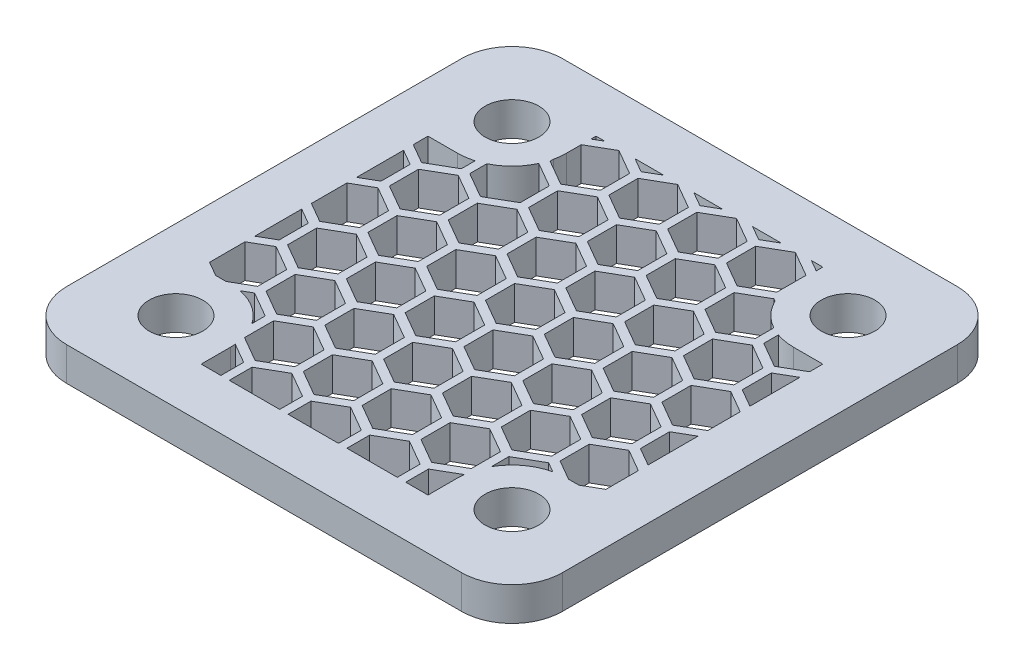
SolidWorks part; units mm, degrees
ref_plane "Front Plane" through (0, 0, 0) normal (0, 0, 1) x (1, 0, 0)
ref_plane "Top Plane" through (0, 0, 0) normal (0, 1, 0) x (1, 0, 0)
ref_plane "Right Plane" through (0, 0, 0) normal (1, 0, 0) x (0, 0, -1)
sketch "Sketch1" plane through (0, 0, 0) normal (0, 1, 0) x (1, 0, 0)
  line L1 (0, 0) -> (29.5, 0)
  line L2 (0, 0) -> (0, 29.5)
  line L3 (0, 29.5) -> (29.5, 29.5)
  line L4 (29.5, 0) -> (29.5, 29.5)
  dimension "D1" = 29.5
extrude "Boss-Extrude1" add sketch "Sketch1" along normal blind 20.5
fillet "Fillet1" radius 3 4 edges at (0, 10.25, -29.5) (29.5, 10.25, -29.5) (29.5, 10.25, 0) (0, 10.25, 0)
shell "Shell1" thickness 2 removed face at (14.75, 20.5, -14.75)
sketch "Sketch2" plane through (0, 0, 0) normal (0, -1, 0) x (1, 0, 0)
  line L1164 (2.4229, -2.1927) -> (3.9229, -1.3266)
  line L1165 (3.9229, -1.3266) -> (3.9229, 0.4054)
  line L1166 (3.9229, 0.4054) -> (2.4229, 1.2714)
  line L1167 (2.4229, 1.2714) -> (0.9229, 0.4054)
  line L1168 (0.9229, 0.4054) -> (0.9229, -1.3266)
  line L1169 (0.9229, -1.3266) -> (2.4229, -2.1927)
  line L1170 (4.1729, -1.7597) -> (2.6729, -2.6257)
  line L1171 (2.6729, -2.6257) -> (2.6729, -4.3577)
  line L1172 (2.6729, -4.3577) -> (4.1729, -5.2238)
  line L1173 (4.1729, -5.2238) -> (5.6729, -4.3577)
  line L1174 (5.6729, -4.3577) -> (5.6729, -2.6257)
  line L1175 (5.6729, -2.6257) -> (4.1729, -1.7597)
  line L1176 (5.9229, -2.1927) -> (7.4229, -1.3266)
  line L1177 (7.4229, -1.3266) -> (7.4229, 0.4054)
  line L1178 (7.4229, 0.4054) -> (5.9229, 1.2714)
  line L1179 (5.9229, 1.2714) -> (4.4229, 0.4054)
  line L1180 (4.4229, 0.4054) -> (4.4229, -1.3266)
  line L1181 (4.4229, -1.3266) -> (5.9229, -2.1927)
  line L1182 (7.6729, -1.7597) -> (6.1729, -2.6257)
  line L1183 (6.1729, -2.6257) -> (6.1729, -4.3577)
  line L1184 (6.1729, -4.3577) -> (7.6729, -5.2238)
  line L1185 (7.6729, -5.2238) -> (9.1729, -4.3577)
  line L1186 (9.1729, -4.3577) -> (9.1729, -2.6257)
  line L1187 (9.1729, -2.6257) -> (7.6729, -1.7597)
  line L1188 (9.4229, -2.1927) -> (10.9229, -1.3266)
  line L1189 (10.9229, -1.3266) -> (10.9229, 0.4054)
  line L1190 (10.9229, 0.4054) -> (9.4229, 1.2714)
  line L1191 (9.4229, 1.2714) -> (7.9229, 0.4054)
  line L1192 (7.9229, 0.4054) -> (7.9229, -1.3266)
  line L1193 (7.9229, -1.3266) -> (9.4229, -2.1927)
  line L1194 (11.1729, -1.7597) -> (9.6729, -2.6257)
  line L1195 (9.6729, -2.6257) -> (9.6729, -4.3577)
  line L1196 (9.6729, -4.3577) -> (11.1729, -5.2238)
  line L1197 (11.1729, -5.2238) -> (12.6729, -4.3577)
  line L1198 (12.6729, -4.3577) -> (12.6729, -2.6257)
  line L1199 (12.6729, -2.6257) -> (11.1729, -1.7597)
  line L1200 (12.9229, -2.1927) -> (14.4229, -1.3266)
  line L1201 (14.4229, -1.3266) -> (14.4229, 0.4054)
  line L1202 (14.4229, 0.4054) -> (12.9229, 1.2714)
  line L1203 (12.9229, 1.2714) -> (11.4229, 0.4054)
  line L1204 (11.4229, 0.4054) -> (11.4229, -1.3266)
  line L1205 (11.4229, -1.3266) -> (12.9229, -2.1927)
  line L1206 (14.6729, -1.7597) -> (13.1729, -2.6257)
  line L1207 (13.1729, -2.6257) -> (13.1729, -4.3577)
  line L1208 (13.1729, -4.3577) -> (14.6729, -5.2238)
  line L1209 (14.6729, -5.2238) -> (16.1729, -4.3577)
  line L1210 (16.1729, -4.3577) -> (16.1729, -2.6257)
  line L1211 (16.1729, -2.6257) -> (14.6729, -1.7597)
  line L1212 (16.4229, -2.1927) -> (17.9229, -1.3266)
  line L1213 (17.9229, -1.3266) -> (17.9229, 0.4054)
  line L1214 (17.9229, 0.4054) -> (16.4229, 1.2714)
  line L1215 (16.4229, 1.2714) -> (14.9229, 0.4054)
  line L1216 (14.9229, 0.4054) -> (14.9229, -1.3266)
  line L1217 (14.9229, -1.3266) -> (16.4229, -2.1927)
  line L1218 (18.1729, -1.7597) -> (16.6729, -2.6257)
  line L1219 (16.6729, -2.6257) -> (16.6729, -4.3577)
  line L1220 (16.6729, -4.3577) -> (18.1729, -5.2238)
  line L1221 (18.1729, -5.2238) -> (19.6729, -4.3577)
  line L1222 (19.6729, -4.3577) -> (19.6729, -2.6257)
  line L1223 (19.6729, -2.6257) -> (18.1729, -1.7597)
  line L1224 (19.9229, -2.1927) -> (21.4229, -1.3266)
  line L1225 (21.4229, -1.3266) -> (21.4229, 0.4054)
  line L1226 (21.4229, 0.4054) -> (19.9229, 1.2714)
  line L1227 (19.9229, 1.2714) -> (18.4229, 0.4054)
  line L1228 (18.4229, 0.4054) -> (18.4229, -1.3266)
  line L1229 (18.4229, -1.3266) -> (19.9229, -2.1927)
  line L1230 (21.6729, -1.7597) -> (20.1729, -2.6257)
  line L1231 (20.1729, -2.6257) -> (20.1729, -4.3577)
  line L1232 (20.1729, -4.3577) -> (21.6729, -5.2238)
  line L1233 (21.6729, -5.2238) -> (23.1729, -4.3577)
  line L1234 (23.1729, -4.3577) -> (23.1729, -2.6257)
  line L1235 (23.1729, -2.6257) -> (21.6729, -1.7597)
  line L1236 (23.4229, -2.1927) -> (24.9229, -1.3266)
  line L1237 (24.9229, -1.3266) -> (24.9229, 0.4054)
  line L1238 (24.9229, 0.4054) -> (23.4229, 1.2714)
  line L1239 (23.4229, 1.2714) -> (21.9229, 0.4054)
  line L1240 (21.9229, 0.4054) -> (21.9229, -1.3266)
  line L1241 (21.9229, -1.3266) -> (23.4229, -2.1927)
  line L1242 (25.1729, -1.7597) -> (23.6729, -2.6257)
  line L1243 (23.6729, -2.6257) -> (23.6729, -4.3577)
  line L1244 (23.6729, -4.3577) -> (25.1729, -5.2238)
  line L1245 (25.1729, -5.2238) -> (26.6729, -4.3577)
  line L1246 (26.6729, -4.3577) -> (26.6729, -2.6257)
  line L1247 (26.6729, -2.6257) -> (25.1729, -1.7597)
  line L1248 (26.9229, -2.1927) -> (28.4229, -1.3266)
  line L1249 (28.4229, -1.3266) -> (28.4229, 0.4054)
  line L1250 (28.4229, 0.4054) -> (26.9229, 1.2714)
  line L1251 (26.9229, 1.2714) -> (25.4229, 0.4054)
  line L1252 (25.4229, 0.4054) -> (25.4229, -1.3266)
  line L1253 (25.4229, -1.3266) -> (26.9229, -2.1927)
  line L1254 (28.6729, -1.7597) -> (27.1729, -2.6257)
  line L1255 (27.1729, -2.6257) -> (27.1729, -4.3577)
  line L1256 (27.1729, -4.3577) -> (28.6729, -5.2238)
  line L1257 (28.6729, -5.2238) -> (30.1729, -4.3577)
  line L1258 (30.1729, -4.3577) -> (30.1729, -2.6257)
  line L1259 (30.1729, -2.6257) -> (28.6729, -1.7597)
  line L1260 (30.4229, -2.1927) -> (31.9229, -1.3266)
  line L1261 (31.9229, -1.3266) -> (31.9229, 0.4054)
  line L1262 (31.9229, 0.4054) -> (30.4229, 1.2714)
  line L1263 (30.4229, 1.2714) -> (28.9229, 0.4054)
  line L1264 (28.9229, 0.4054) -> (28.9229, -1.3266)
  line L1265 (28.9229, -1.3266) -> (30.4229, -2.1927)
  line L1266 (32.1729, -1.7597) -> (30.6729, -2.6257)
  line L1267 (30.6729, -2.6257) -> (30.6729, -4.3577)
  line L1268 (30.6729, -4.3577) -> (32.1729, -5.2238)
  line L1269 (32.1729, -5.2238) -> (33.6729, -4.3577)
  line L1270 (33.6729, -4.3577) -> (33.6729, -2.6257)
  line L1271 (33.6729, -2.6257) -> (32.1729, -1.7597)
  line L1272 (33.9229, -2.1927) -> (35.4229, -1.3266)
  line L1273 (35.4229, -1.3266) -> (35.4229, 0.4054)
  line L1274 (35.4229, 0.4054) -> (33.9229, 1.2714)
  line L1275 (33.9229, 1.2714) -> (32.4229, 0.4054)
  line L1276 (32.4229, 0.4054) -> (32.4229, -1.3266)
  line L1277 (32.4229, -1.3266) -> (33.9229, -2.1927)
  line L1278 (35.6729, -1.7597) -> (34.1729, -2.6257)
  line L1279 (34.1729, -2.6257) -> (34.1729, -4.3577)
  line L1280 (34.1729, -4.3577) -> (35.6729, -5.2238)
  line L1281 (35.6729, -5.2238) -> (37.1729, -4.3577)
  line L1282 (37.1729, -4.3577) -> (37.1729, -2.6257)
  line L1283 (37.1729, -2.6257) -> (35.6729, -1.7597)
  line L1284 (37.4229, -2.1927) -> (38.9229, -1.3266)
  line L1285 (38.9229, -1.3266) -> (38.9229, 0.4054)
  line L1286 (38.9229, 0.4054) -> (37.4229, 1.2714)
  line L1287 (37.4229, 1.2714) -> (35.9229, 0.4054)
  line L1288 (35.9229, 0.4054) -> (35.9229, -1.3266)
  line L1289 (35.9229, -1.3266) -> (37.4229, -2.1927)
  line L1290 (39.1729, -1.7597) -> (37.6729, -2.6257)
  line L1291 (37.6729, -2.6257) -> (37.6729, -4.3577)
  line L1292 (37.6729, -4.3577) -> (39.1729, -5.2238)
  line L1293 (39.1729, -5.2238) -> (40.6729, -4.3577)
  line L1294 (40.6729, -4.3577) -> (40.6729, -2.6257)
  line L1295 (40.6729, -2.6257) -> (39.1729, -1.7597)
  line L1296 (40.9229, -2.1927) -> (42.4229, -1.3266)
  line L1297 (42.4229, -1.3266) -> (42.4229, 0.4054)
  line L1298 (42.4229, 0.4054) -> (40.9229, 1.2714)
  line L1299 (40.9229, 1.2714) -> (39.4229, 0.4054)
  line L1300 (39.4229, 0.4054) -> (39.4229, -1.3266)
  line L1301 (39.4229, -1.3266) -> (40.9229, -2.1927)
  line L1302 (42.6729, -1.7597) -> (41.1729, -2.6257)
  line L1303 (41.1729, -2.6257) -> (41.1729, -4.3577)
  line L1304 (41.1729, -4.3577) -> (42.6729, -5.2238)
  line L1305 (42.6729, -5.2238) -> (44.1729, -4.3577)
  line L1306 (44.1729, -4.3577) -> (44.1729, -2.6257)
  line L1307 (44.1729, -2.6257) -> (42.6729, -1.7597)
  line L1308 (44.4229, -2.1927) -> (45.9229, -1.3266)
  line L1309 (45.9229, -1.3266) -> (45.9229, 0.4054)
  line L1310 (45.9229, 0.4054) -> (44.4229, 1.2714)
  line L1311 (44.4229, 1.2714) -> (42.9229, 0.4054)
  line L1312 (42.9229, 0.4054) -> (42.9229, -1.3266)
  line L1313 (42.9229, -1.3266) -> (44.4229, -2.1927)
  line L1356 (2.4229, -8.2549) -> (3.9229, -7.3888)
  line L1357 (3.9229, -7.3888) -> (3.9229, -5.6568)
  line L1358 (3.9229, -5.6568) -> (2.4229, -4.7908)
  line L1359 (2.4229, -4.7908) -> (0.9229, -5.6568)
  line L1360 (0.9229, -5.6568) -> (0.9229, -7.3888)
  line L1361 (0.9229, -7.3888) -> (2.4229, -8.2549)
  line L1362 (4.1729, -7.8218) -> (2.6729, -8.6879)
  line L1363 (2.6729, -8.6879) -> (2.6729, -10.4199)
  line L1364 (2.6729, -10.4199) -> (4.1729, -11.2859)
  line L1365 (4.1729, -11.2859) -> (5.6729, -10.4199)
  line L1366 (5.6729, -10.4199) -> (5.6729, -8.6879)
  line L1367 (5.6729, -8.6879) -> (4.1729, -7.8218)
  line L1368 (5.9229, -8.2549) -> (7.4229, -7.3888)
  line L1369 (7.4229, -7.3888) -> (7.4229, -5.6568)
  line L1370 (7.4229, -5.6568) -> (5.9229, -4.7908)
  line L1371 (5.9229, -4.7908) -> (4.4229, -5.6568)
  line L1372 (4.4229, -5.6568) -> (4.4229, -7.3888)
  line L1373 (4.4229, -7.3888) -> (5.9229, -8.2549)
  line L1374 (7.6729, -7.8218) -> (6.1729, -8.6879)
  line L1375 (6.1729, -8.6879) -> (6.1729, -10.4199)
  line L1376 (6.1729, -10.4199) -> (7.6729, -11.2859)
  line L1377 (7.6729, -11.2859) -> (9.1729, -10.4199)
  line L1378 (9.1729, -10.4199) -> (9.1729, -8.6879)
  line L1379 (9.1729, -8.6879) -> (7.6729, -7.8218)
  line L1380 (9.4229, -8.2549) -> (10.9229, -7.3888)
  line L1381 (10.9229, -7.3888) -> (10.9229, -5.6568)
  line L1382 (10.9229, -5.6568) -> (9.4229, -4.7908)
  line L1383 (9.4229, -4.7908) -> (7.9229, -5.6568)
  line L1384 (7.9229, -5.6568) -> (7.9229, -7.3888)
  line L1385 (7.9229, -7.3888) -> (9.4229, -8.2549)
  line L1386 (11.1729, -7.8218) -> (9.6729, -8.6879)
  line L1387 (9.6729, -8.6879) -> (9.6729, -10.4199)
  line L1388 (9.6729, -10.4199) -> (11.1729, -11.2859)
  line L1389 (11.1729, -11.2859) -> (12.6729, -10.4199)
  line L1390 (12.6729, -10.4199) -> (12.6729, -8.6879)
  line L1391 (12.6729, -8.6879) -> (11.1729, -7.8218)
  line L1392 (12.9229, -8.2549) -> (14.4229, -7.3888)
  line L1393 (14.4229, -7.3888) -> (14.4229, -5.6568)
  line L1394 (14.4229, -5.6568) -> (12.9229, -4.7908)
  line L1395 (12.9229, -4.7908) -> (11.4229, -5.6568)
  line L1396 (11.4229, -5.6568) -> (11.4229, -7.3888)
  line L1397 (11.4229, -7.3888) -> (12.9229, -8.2549)
  line L1398 (14.6729, -7.8218) -> (13.1729, -8.6879)
  line L1399 (13.1729, -8.6879) -> (13.1729, -10.4199)
  line L1400 (13.1729, -10.4199) -> (14.6729, -11.2859)
  line L1401 (14.6729, -11.2859) -> (16.1729, -10.4199)
  line L1402 (16.1729, -10.4199) -> (16.1729, -8.6879)
  line L1403 (16.1729, -8.6879) -> (14.6729, -7.8218)
  line L1404 (16.4229, -8.2549) -> (17.9229, -7.3888)
  line L1405 (17.9229, -7.3888) -> (17.9229, -5.6568)
  line L1406 (17.9229, -5.6568) -> (16.4229, -4.7908)
  line L1407 (16.4229, -4.7908) -> (14.9229, -5.6568)
  line L1408 (14.9229, -5.6568) -> (14.9229, -7.3888)
  line L1409 (14.9229, -7.3888) -> (16.4229, -8.2549)
  line L1410 (18.1729, -7.8218) -> (16.6729, -8.6879)
  line L1411 (16.6729, -8.6879) -> (16.6729, -10.4199)
  line L1412 (16.6729, -10.4199) -> (18.1729, -11.2859)
  line L1413 (18.1729, -11.2859) -> (19.6729, -10.4199)
  line L1414 (19.6729, -10.4199) -> (19.6729, -8.6879)
  line L1415 (19.6729, -8.6879) -> (18.1729, -7.8218)
  line L1416 (19.9229, -8.2549) -> (21.4229, -7.3888)
  line L1417 (21.4229, -7.3888) -> (21.4229, -5.6568)
  line L1418 (21.4229, -5.6568) -> (19.9229, -4.7908)
  line L1419 (19.9229, -4.7908) -> (18.4229, -5.6568)
  line L1420 (18.4229, -5.6568) -> (18.4229, -7.3888)
  line L1421 (18.4229, -7.3888) -> (19.9229, -8.2549)
  line L1422 (21.6729, -7.8218) -> (20.1729, -8.6879)
  line L1423 (20.1729, -8.6879) -> (20.1729, -10.4199)
  line L1424 (20.1729, -10.4199) -> (21.6729, -11.2859)
  line L1425 (21.6729, -11.2859) -> (23.1729, -10.4199)
  line L1426 (23.1729, -10.4199) -> (23.1729, -8.6879)
  line L1427 (23.1729, -8.6879) -> (21.6729, -7.8218)
  line L1428 (23.4229, -8.2549) -> (24.9229, -7.3888)
  line L1429 (24.9229, -7.3888) -> (24.9229, -5.6568)
  line L1430 (24.9229, -5.6568) -> (23.4229, -4.7908)
  line L1431 (23.4229, -4.7908) -> (21.9229, -5.6568)
  line L1432 (21.9229, -5.6568) -> (21.9229, -7.3888)
  line L1433 (21.9229, -7.3888) -> (23.4229, -8.2549)
  line L1434 (25.1729, -7.8218) -> (23.6729, -8.6879)
  line L1435 (23.6729, -8.6879) -> (23.6729, -10.4199)
  line L1436 (23.6729, -10.4199) -> (25.1729, -11.2859)
  line L1437 (25.1729, -11.2859) -> (26.6729, -10.4199)
  line L1438 (26.6729, -10.4199) -> (26.6729, -8.6879)
  line L1439 (26.6729, -8.6879) -> (25.1729, -7.8218)
  line L1440 (26.9229, -8.2549) -> (28.4229, -7.3888)
  line L1441 (28.4229, -7.3888) -> (28.4229, -5.6568)
  line L1442 (28.4229, -5.6568) -> (26.9229, -4.7908)
  line L1443 (26.9229, -4.7908) -> (25.4229, -5.6568)
  line L1444 (25.4229, -5.6568) -> (25.4229, -7.3888)
  line L1445 (25.4229, -7.3888) -> (26.9229, -8.2549)
  line L1446 (28.6729, -7.8218) -> (27.1729, -8.6879)
  line L1447 (27.1729, -8.6879) -> (27.1729, -10.4199)
  line L1448 (27.1729, -10.4199) -> (28.6729, -11.2859)
  line L1449 (28.6729, -11.2859) -> (30.1729, -10.4199)
  line L1450 (30.1729, -10.4199) -> (30.1729, -8.6879)
  line L1451 (30.1729, -8.6879) -> (28.6729, -7.8218)
  line L1452 (30.4229, -8.2549) -> (31.9229, -7.3888)
  line L1453 (31.9229, -7.3888) -> (31.9229, -5.6568)
  line L1454 (31.9229, -5.6568) -> (30.4229, -4.7908)
  line L1455 (30.4229, -4.7908) -> (28.9229, -5.6568)
  line L1456 (28.9229, -5.6568) -> (28.9229, -7.3888)
  line L1457 (28.9229, -7.3888) -> (30.4229, -8.2549)
  line L1458 (32.1729, -7.8218) -> (30.6729, -8.6879)
  line L1459 (30.6729, -8.6879) -> (30.6729, -10.4199)
  line L1460 (30.6729, -10.4199) -> (32.1729, -11.2859)
  line L1461 (32.1729, -11.2859) -> (33.6729, -10.4199)
  line L1462 (33.6729, -10.4199) -> (33.6729, -8.6879)
  line L1463 (33.6729, -8.6879) -> (32.1729, -7.8218)
  line L1464 (33.9229, -8.2549) -> (35.4229, -7.3888)
  line L1465 (35.4229, -7.3888) -> (35.4229, -5.6568)
  line L1466 (35.4229, -5.6568) -> (33.9229, -4.7908)
  line L1467 (33.9229, -4.7908) -> (32.4229, -5.6568)
  line L1468 (32.4229, -5.6568) -> (32.4229, -7.3888)
  line L1469 (32.4229, -7.3888) -> (33.9229, -8.2549)
  line L1470 (35.6729, -7.8218) -> (34.1729, -8.6879)
  line L1471 (34.1729, -8.6879) -> (34.1729, -10.4199)
  line L1472 (34.1729, -10.4199) -> (35.6729, -11.2859)
  line L1473 (35.6729, -11.2859) -> (37.1729, -10.4199)
  line L1474 (37.1729, -10.4199) -> (37.1729, -8.6879)
  line L1475 (37.1729, -8.6879) -> (35.6729, -7.8218)
  line L1476 (37.4229, -8.2549) -> (38.9229, -7.3888)
  line L1477 (38.9229, -7.3888) -> (38.9229, -5.6568)
  line L1478 (38.9229, -5.6568) -> (37.4229, -4.7908)
  line L1479 (37.4229, -4.7908) -> (35.9229, -5.6568)
  line L1480 (35.9229, -5.6568) -> (35.9229, -7.3888)
  line L1481 (35.9229, -7.3888) -> (37.4229, -8.2549)
  line L1482 (39.1729, -7.8218) -> (37.6729, -8.6879)
  line L1483 (37.6729, -8.6879) -> (37.6729, -10.4199)
  line L1484 (37.6729, -10.4199) -> (39.1729, -11.2859)
  line L1485 (39.1729, -11.2859) -> (40.6729, -10.4199)
  line L1486 (40.6729, -10.4199) -> (40.6729, -8.6879)
  line L1487 (40.6729, -8.6879) -> (39.1729, -7.8218)
  line L1488 (40.9229, -8.2549) -> (42.4229, -7.3888)
  line L1489 (42.4229, -7.3888) -> (42.4229, -5.6568)
  line L1490 (42.4229, -5.6568) -> (40.9229, -4.7908)
  line L1491 (40.9229, -4.7908) -> (39.4229, -5.6568)
  line L1492 (39.4229, -5.6568) -> (39.4229, -7.3888)
  line L1493 (39.4229, -7.3888) -> (40.9229, -8.2549)
  line L1494 (42.6729, -7.8218) -> (41.1729, -8.6879)
  line L1495 (41.1729, -8.6879) -> (41.1729, -10.4199)
  line L1496 (41.1729, -10.4199) -> (42.6729, -11.2859)
  line L1497 (42.6729, -11.2859) -> (44.1729, -10.4199)
  line L1498 (44.1729, -10.4199) -> (44.1729, -8.6879)
  line L1499 (44.1729, -8.6879) -> (42.6729, -7.8218)
  line L1500 (44.4229, -8.2549) -> (45.9229, -7.3888)
  line L1501 (45.9229, -7.3888) -> (45.9229, -5.6568)
  line L1502 (45.9229, -5.6568) -> (44.4229, -4.7908)
  line L1503 (44.4229, -4.7908) -> (42.9229, -5.6568)
  line L1504 (42.9229, -5.6568) -> (42.9229, -7.3888)
  line L1505 (42.9229, -7.3888) -> (44.4229, -8.2549)
  line L1548 (2.4229, -14.3171) -> (3.9229, -13.451)
  line L1549 (3.9229, -13.451) -> (3.9229, -11.719)
  line L1550 (3.9229, -11.719) -> (2.4229, -10.853)
  line L1551 (2.4229, -10.853) -> (0.9229, -11.719)
  line L1552 (0.9229, -11.719) -> (0.9229, -13.451)
  line L1553 (0.9229, -13.451) -> (2.4229, -14.3171)
  line L1554 (4.1729, -13.884) -> (2.6729, -14.7501)
  line L1555 (2.6729, -14.7501) -> (2.6729, -16.4821)
  line L1556 (2.6729, -16.4821) -> (4.1729, -17.3481)
  line L1557 (4.1729, -17.3481) -> (5.6729, -16.4821)
  line L1558 (5.6729, -16.4821) -> (5.6729, -14.7501)
  line L1559 (5.6729, -14.7501) -> (4.1729, -13.884)
  line L1560 (5.9229, -14.3171) -> (7.4229, -13.451)
  line L1561 (7.4229, -13.451) -> (7.4229, -11.719)
  line L1562 (7.4229, -11.719) -> (5.9229, -10.853)
  line L1563 (5.9229, -10.853) -> (4.4229, -11.719)
  line L1564 (4.4229, -11.719) -> (4.4229, -13.451)
  line L1565 (4.4229, -13.451) -> (5.9229, -14.3171)
  line L1566 (7.6729, -13.884) -> (6.1729, -14.7501)
  line L1567 (6.1729, -14.7501) -> (6.1729, -16.4821)
  line L1568 (6.1729, -16.4821) -> (7.6729, -17.3481)
  line L1569 (7.6729, -17.3481) -> (9.1729, -16.4821)
  line L1570 (9.1729, -16.4821) -> (9.1729, -14.7501)
  line L1571 (9.1729, -14.7501) -> (7.6729, -13.884)
  line L1572 (9.4229, -14.3171) -> (10.9229, -13.451)
  line L1573 (10.9229, -13.451) -> (10.9229, -11.719)
  line L1574 (10.9229, -11.719) -> (9.4229, -10.853)
  line L1575 (9.4229, -10.853) -> (7.9229, -11.719)
  line L1576 (7.9229, -11.719) -> (7.9229, -13.451)
  line L1577 (7.9229, -13.451) -> (9.4229, -14.3171)
  line L1578 (11.1729, -13.884) -> (9.6729, -14.7501)
  line L1579 (9.6729, -14.7501) -> (9.6729, -16.4821)
  line L1580 (9.6729, -16.4821) -> (11.1729, -17.3481)
  line L1581 (11.1729, -17.3481) -> (12.6729, -16.4821)
  line L1582 (12.6729, -16.4821) -> (12.6729, -14.7501)
  line L1583 (12.6729, -14.7501) -> (11.1729, -13.884)
  line L1584 (12.9229, -14.3171) -> (14.4229, -13.451)
  line L1585 (14.4229, -13.451) -> (14.4229, -11.719)
  line L1586 (14.4229, -11.719) -> (12.9229, -10.853)
  line L1587 (12.9229, -10.853) -> (11.4229, -11.719)
  line L1588 (11.4229, -11.719) -> (11.4229, -13.451)
  line L1589 (11.4229, -13.451) -> (12.9229, -14.3171)
  line L1590 (14.6729, -13.884) -> (13.1729, -14.7501)
  line L1591 (13.1729, -14.7501) -> (13.1729, -16.4821)
  line L1592 (13.1729, -16.4821) -> (14.6729, -17.3481)
  line L1593 (14.6729, -17.3481) -> (16.1729, -16.4821)
  line L1594 (16.1729, -16.4821) -> (16.1729, -14.7501)
  line L1595 (16.1729, -14.7501) -> (14.6729, -13.884)
  line L1596 (16.4229, -14.3171) -> (17.9229, -13.451)
  line L1597 (17.9229, -13.451) -> (17.9229, -11.719)
  line L1598 (17.9229, -11.719) -> (16.4229, -10.853)
  line L1599 (16.4229, -10.853) -> (14.9229, -11.719)
  line L1600 (14.9229, -11.719) -> (14.9229, -13.451)
  line L1601 (14.9229, -13.451) -> (16.4229, -14.3171)
  line L1602 (18.1729, -13.884) -> (16.6729, -14.7501)
  line L1603 (16.6729, -14.7501) -> (16.6729, -16.4821)
  line L1604 (16.6729, -16.4821) -> (18.1729, -17.3481)
  line L1605 (18.1729, -17.3481) -> (19.6729, -16.4821)
  line L1606 (19.6729, -16.4821) -> (19.6729, -14.7501)
  line L1607 (19.6729, -14.7501) -> (18.1729, -13.884)
  line L1608 (19.9229, -14.3171) -> (21.4229, -13.451)
  line L1609 (21.4229, -13.451) -> (21.4229, -11.719)
  line L1610 (21.4229, -11.719) -> (19.9229, -10.853)
  line L1611 (19.9229, -10.853) -> (18.4229, -11.719)
  line L1612 (18.4229, -11.719) -> (18.4229, -13.451)
  line L1613 (18.4229, -13.451) -> (19.9229, -14.3171)
  line L1614 (21.6729, -13.884) -> (20.1729, -14.7501)
  line L1615 (20.1729, -14.7501) -> (20.1729, -16.4821)
  line L1616 (20.1729, -16.4821) -> (21.6729, -17.3481)
  line L1617 (21.6729, -17.3481) -> (23.1729, -16.4821)
  line L1618 (23.1729, -16.4821) -> (23.1729, -14.7501)
  line L1619 (23.1729, -14.7501) -> (21.6729, -13.884)
  line L1620 (23.4229, -14.3171) -> (24.9229, -13.451)
  line L1621 (24.9229, -13.451) -> (24.9229, -11.719)
  line L1622 (24.9229, -11.719) -> (23.4229, -10.853)
  line L1623 (23.4229, -10.853) -> (21.9229, -11.719)
  line L1624 (21.9229, -11.719) -> (21.9229, -13.451)
  line L1625 (21.9229, -13.451) -> (23.4229, -14.3171)
  line L1626 (25.1729, -13.884) -> (23.6729, -14.7501)
  line L1627 (23.6729, -14.7501) -> (23.6729, -16.4821)
  line L1628 (23.6729, -16.4821) -> (25.1729, -17.3481)
  line L1629 (25.1729, -17.3481) -> (26.6729, -16.4821)
  line L1630 (26.6729, -16.4821) -> (26.6729, -14.7501)
  line L1631 (26.6729, -14.7501) -> (25.1729, -13.884)
  line L1632 (26.9229, -14.3171) -> (28.4229, -13.451)
  line L1633 (28.4229, -13.451) -> (28.4229, -11.719)
  line L1634 (28.4229, -11.719) -> (26.9229, -10.853)
  line L1635 (26.9229, -10.853) -> (25.4229, -11.719)
  line L1636 (25.4229, -11.719) -> (25.4229, -13.451)
  line L1637 (25.4229, -13.451) -> (26.9229, -14.3171)
  line L1638 (28.6729, -13.884) -> (27.1729, -14.7501)
  line L1639 (27.1729, -14.7501) -> (27.1729, -16.4821)
  line L1640 (27.1729, -16.4821) -> (28.6729, -17.3481)
  line L1641 (28.6729, -17.3481) -> (30.1729, -16.4821)
  line L1642 (30.1729, -16.4821) -> (30.1729, -14.7501)
  line L1643 (30.1729, -14.7501) -> (28.6729, -13.884)
  line L1644 (30.4229, -14.3171) -> (31.9229, -13.451)
  line L1645 (31.9229, -13.451) -> (31.9229, -11.719)
  line L1646 (31.9229, -11.719) -> (30.4229, -10.853)
  line L1647 (30.4229, -10.853) -> (28.9229, -11.719)
  line L1648 (28.9229, -11.719) -> (28.9229, -13.451)
  line L1649 (28.9229, -13.451) -> (30.4229, -14.3171)
  line L1650 (32.1729, -13.884) -> (30.6729, -14.7501)
  line L1651 (30.6729, -14.7501) -> (30.6729, -16.4821)
  line L1652 (30.6729, -16.4821) -> (32.1729, -17.3481)
  line L1653 (32.1729, -17.3481) -> (33.6729, -16.4821)
  line L1654 (33.6729, -16.4821) -> (33.6729, -14.7501)
  line L1655 (33.6729, -14.7501) -> (32.1729, -13.884)
  line L1656 (33.9229, -14.3171) -> (35.4229, -13.451)
  line L1657 (35.4229, -13.451) -> (35.4229, -11.719)
  line L1658 (35.4229, -11.719) -> (33.9229, -10.853)
  line L1659 (33.9229, -10.853) -> (32.4229, -11.719)
  line L1660 (32.4229, -11.719) -> (32.4229, -13.451)
  line L1661 (32.4229, -13.451) -> (33.9229, -14.3171)
  line L1662 (35.6729, -13.884) -> (34.1729, -14.7501)
  line L1663 (34.1729, -14.7501) -> (34.1729, -16.4821)
  line L1664 (34.1729, -16.4821) -> (35.6729, -17.3481)
  line L1665 (35.6729, -17.3481) -> (37.1729, -16.4821)
  line L1666 (37.1729, -16.4821) -> (37.1729, -14.7501)
  line L1667 (37.1729, -14.7501) -> (35.6729, -13.884)
  line L1668 (37.4229, -14.3171) -> (38.9229, -13.451)
  line L1669 (38.9229, -13.451) -> (38.9229, -11.719)
  line L1670 (38.9229, -11.719) -> (37.4229, -10.853)
  line L1671 (37.4229, -10.853) -> (35.9229, -11.719)
  line L1672 (35.9229, -11.719) -> (35.9229, -13.451)
  line L1673 (35.9229, -13.451) -> (37.4229, -14.3171)
  line L1674 (39.1729, -13.884) -> (37.6729, -14.7501)
  line L1675 (37.6729, -14.7501) -> (37.6729, -16.4821)
  line L1676 (37.6729, -16.4821) -> (39.1729, -17.3481)
  line L1677 (39.1729, -17.3481) -> (40.6729, -16.4821)
  line L1678 (40.6729, -16.4821) -> (40.6729, -14.7501)
  line L1679 (40.6729, -14.7501) -> (39.1729, -13.884)
  line L1680 (40.9229, -14.3171) -> (42.4229, -13.451)
  line L1681 (42.4229, -13.451) -> (42.4229, -11.719)
  line L1682 (42.4229, -11.719) -> (40.9229, -10.853)
  line L1683 (40.9229, -10.853) -> (39.4229, -11.719)
  line L1684 (39.4229, -11.719) -> (39.4229, -13.451)
  line L1685 (39.4229, -13.451) -> (40.9229, -14.3171)
  line L1686 (42.6729, -13.884) -> (41.1729, -14.7501)
  line L1687 (41.1729, -14.7501) -> (41.1729, -16.4821)
  line L1688 (41.1729, -16.4821) -> (42.6729, -17.3481)
  line L1689 (42.6729, -17.3481) -> (44.1729, -16.4821)
  line L1690 (44.1729, -16.4821) -> (44.1729, -14.7501)
  line L1691 (44.1729, -14.7501) -> (42.6729, -13.884)
  line L1692 (44.4229, -14.3171) -> (45.9229, -13.451)
  line L1693 (45.9229, -13.451) -> (45.9229, -11.719)
  line L1694 (45.9229, -11.719) -> (44.4229, -10.853)
  line L1695 (44.4229, -10.853) -> (42.9229, -11.719)
  line L1696 (42.9229, -11.719) -> (42.9229, -13.451)
  line L1697 (42.9229, -13.451) -> (44.4229, -14.3171)
  line L1740 (2.4229, -20.3792) -> (3.9229, -19.5132)
  line L1741 (3.9229, -19.5132) -> (3.9229, -17.7812)
  line L1742 (3.9229, -17.7812) -> (2.4229, -16.9151)
  line L1743 (2.4229, -16.9151) -> (0.9229, -17.7812)
  line L1744 (0.9229, -17.7812) -> (0.9229, -19.5132)
  line L1745 (0.9229, -19.5132) -> (2.4229, -20.3792)
  line L1746 (4.1729, -19.9462) -> (2.6729, -20.8123)
  line L1747 (2.6729, -20.8123) -> (2.6729, -22.5443)
  line L1748 (2.6729, -22.5443) -> (4.1729, -23.4103)
  line L1749 (4.1729, -23.4103) -> (5.6729, -22.5443)
  line L1750 (5.6729, -22.5443) -> (5.6729, -20.8123)
  line L1751 (5.6729, -20.8123) -> (4.1729, -19.9462)
  line L1752 (5.9229, -20.3792) -> (7.4229, -19.5132)
  line L1753 (7.4229, -19.5132) -> (7.4229, -17.7812)
  line L1754 (7.4229, -17.7812) -> (5.9229, -16.9151)
  line L1755 (5.9229, -16.9151) -> (4.4229, -17.7812)
  line L1756 (4.4229, -17.7812) -> (4.4229, -19.5132)
  line L1757 (4.4229, -19.5132) -> (5.9229, -20.3792)
  line L1758 (7.6729, -19.9462) -> (6.1729, -20.8123)
  line L1759 (6.1729, -20.8123) -> (6.1729, -22.5443)
  line L1760 (6.1729, -22.5443) -> (7.6729, -23.4103)
  line L1761 (7.6729, -23.4103) -> (9.1729, -22.5443)
  line L1762 (9.1729, -22.5443) -> (9.1729, -20.8123)
  line L1763 (9.1729, -20.8123) -> (7.6729, -19.9462)
  line L1764 (9.4229, -20.3792) -> (10.9229, -19.5132)
  line L1765 (10.9229, -19.5132) -> (10.9229, -17.7812)
  line L1766 (10.9229, -17.7812) -> (9.4229, -16.9151)
  line L1767 (9.4229, -16.9151) -> (7.9229, -17.7812)
  line L1768 (7.9229, -17.7812) -> (7.9229, -19.5132)
  line L1769 (7.9229, -19.5132) -> (9.4229, -20.3792)
  line L1770 (11.1729, -19.9462) -> (9.6729, -20.8123)
  line L1771 (9.6729, -20.8123) -> (9.6729, -22.5443)
  line L1772 (9.6729, -22.5443) -> (11.1729, -23.4103)
  line L1773 (11.1729, -23.4103) -> (12.6729, -22.5443)
  line L1774 (12.6729, -22.5443) -> (12.6729, -20.8123)
  line L1775 (12.6729, -20.8123) -> (11.1729, -19.9462)
  line L1776 (12.9229, -20.3792) -> (14.4229, -19.5132)
  line L1777 (14.4229, -19.5132) -> (14.4229, -17.7812)
  line L1778 (14.4229, -17.7812) -> (12.9229, -16.9151)
  line L1779 (12.9229, -16.9151) -> (11.4229, -17.7812)
  line L1780 (11.4229, -17.7812) -> (11.4229, -19.5132)
  line L1781 (11.4229, -19.5132) -> (12.9229, -20.3792)
  line L1782 (14.6729, -19.9462) -> (13.1729, -20.8123)
  line L1783 (13.1729, -20.8123) -> (13.1729, -22.5443)
  line L1784 (13.1729, -22.5443) -> (14.6729, -23.4103)
  line L1785 (14.6729, -23.4103) -> (16.1729, -22.5443)
  line L1786 (16.1729, -22.5443) -> (16.1729, -20.8123)
  line L1787 (16.1729, -20.8123) -> (14.6729, -19.9462)
  line L1788 (16.4229, -20.3792) -> (17.9229, -19.5132)
  line L1789 (17.9229, -19.5132) -> (17.9229, -17.7812)
  line L1790 (17.9229, -17.7812) -> (16.4229, -16.9151)
  line L1791 (16.4229, -16.9151) -> (14.9229, -17.7812)
  line L1792 (14.9229, -17.7812) -> (14.9229, -19.5132)
  line L1793 (14.9229, -19.5132) -> (16.4229, -20.3792)
  line L1794 (18.1729, -19.9462) -> (16.6729, -20.8123)
  line L1795 (16.6729, -20.8123) -> (16.6729, -22.5443)
  line L1796 (16.6729, -22.5443) -> (18.1729, -23.4103)
  line L1797 (18.1729, -23.4103) -> (19.6729, -22.5443)
  line L1798 (19.6729, -22.5443) -> (19.6729, -20.8123)
  line L1799 (19.6729, -20.8123) -> (18.1729, -19.9462)
  line L1800 (19.9229, -20.3792) -> (21.4229, -19.5132)
  line L1801 (21.4229, -19.5132) -> (21.4229, -17.7812)
  line L1802 (21.4229, -17.7812) -> (19.9229, -16.9151)
  line L1803 (19.9229, -16.9151) -> (18.4229, -17.7812)
  line L1804 (18.4229, -17.7812) -> (18.4229, -19.5132)
  line L1805 (18.4229, -19.5132) -> (19.9229, -20.3792)
  line L1806 (21.6729, -19.9462) -> (20.1729, -20.8123)
  line L1807 (20.1729, -20.8123) -> (20.1729, -22.5443)
  line L1808 (20.1729, -22.5443) -> (21.6729, -23.4103)
  line L1809 (21.6729, -23.4103) -> (23.1729, -22.5443)
  line L1810 (23.1729, -22.5443) -> (23.1729, -20.8123)
  line L1811 (23.1729, -20.8123) -> (21.6729, -19.9462)
  line L1812 (23.4229, -20.3792) -> (24.9229, -19.5132)
  line L1813 (24.9229, -19.5132) -> (24.9229, -17.7812)
  line L1814 (24.9229, -17.7812) -> (23.4229, -16.9151)
  line L1815 (23.4229, -16.9151) -> (21.9229, -17.7812)
  line L1816 (21.9229, -17.7812) -> (21.9229, -19.5132)
  line L1817 (21.9229, -19.5132) -> (23.4229, -20.3792)
  line L1818 (25.1729, -19.9462) -> (23.6729, -20.8123)
  line L1819 (23.6729, -20.8123) -> (23.6729, -22.5443)
  line L1820 (23.6729, -22.5443) -> (25.1729, -23.4103)
  line L1821 (25.1729, -23.4103) -> (26.6729, -22.5443)
  line L1822 (26.6729, -22.5443) -> (26.6729, -20.8123)
  line L1823 (26.6729, -20.8123) -> (25.1729, -19.9462)
  line L1824 (26.9229, -20.3792) -> (28.4229, -19.5132)
  line L1825 (28.4229, -19.5132) -> (28.4229, -17.7812)
  line L1826 (28.4229, -17.7812) -> (26.9229, -16.9151)
  line L1827 (26.9229, -16.9151) -> (25.4229, -17.7812)
  line L1828 (25.4229, -17.7812) -> (25.4229, -19.5132)
  line L1829 (25.4229, -19.5132) -> (26.9229, -20.3792)
  line L1830 (28.6729, -19.9462) -> (27.1729, -20.8123)
  line L1831 (27.1729, -20.8123) -> (27.1729, -22.5443)
  line L1832 (27.1729, -22.5443) -> (28.6729, -23.4103)
  line L1833 (28.6729, -23.4103) -> (30.1729, -22.5443)
  line L1834 (30.1729, -22.5443) -> (30.1729, -20.8123)
  line L1835 (30.1729, -20.8123) -> (28.6729, -19.9462)
  line L1836 (30.4229, -20.3792) -> (31.9229, -19.5132)
  line L1837 (31.9229, -19.5132) -> (31.9229, -17.7812)
  line L1838 (31.9229, -17.7812) -> (30.4229, -16.9151)
  line L1839 (30.4229, -16.9151) -> (28.9229, -17.7812)
  line L1840 (28.9229, -17.7812) -> (28.9229, -19.5132)
  line L1841 (28.9229, -19.5132) -> (30.4229, -20.3792)
  line L1842 (32.1729, -19.9462) -> (30.6729, -20.8123)
  line L1843 (30.6729, -20.8123) -> (30.6729, -22.5443)
  line L1844 (30.6729, -22.5443) -> (32.1729, -23.4103)
  line L1845 (32.1729, -23.4103) -> (33.6729, -22.5443)
  line L1846 (33.6729, -22.5443) -> (33.6729, -20.8123)
  line L1847 (33.6729, -20.8123) -> (32.1729, -19.9462)
  line L1848 (33.9229, -20.3792) -> (35.4229, -19.5132)
  line L1849 (35.4229, -19.5132) -> (35.4229, -17.7812)
  line L1850 (35.4229, -17.7812) -> (33.9229, -16.9151)
  line L1851 (33.9229, -16.9151) -> (32.4229, -17.7812)
  line L1852 (32.4229, -17.7812) -> (32.4229, -19.5132)
  line L1853 (32.4229, -19.5132) -> (33.9229, -20.3792)
  line L1854 (35.6729, -19.9462) -> (34.1729, -20.8123)
  line L1855 (34.1729, -20.8123) -> (34.1729, -22.5443)
  line L1856 (34.1729, -22.5443) -> (35.6729, -23.4103)
  line L1857 (35.6729, -23.4103) -> (37.1729, -22.5443)
  line L1858 (37.1729, -22.5443) -> (37.1729, -20.8123)
  line L1859 (37.1729, -20.8123) -> (35.6729, -19.9462)
  line L1860 (37.4229, -20.3792) -> (38.9229, -19.5132)
  line L1861 (38.9229, -19.5132) -> (38.9229, -17.7812)
  line L1862 (38.9229, -17.7812) -> (37.4229, -16.9151)
  line L1863 (37.4229, -16.9151) -> (35.9229, -17.7812)
  line L1864 (35.9229, -17.7812) -> (35.9229, -19.5132)
  line L1865 (35.9229, -19.5132) -> (37.4229, -20.3792)
  line L1866 (39.1729, -19.9462) -> (37.6729, -20.8123)
  line L1867 (37.6729, -20.8123) -> (37.6729, -22.5443)
  line L1868 (37.6729, -22.5443) -> (39.1729, -23.4103)
  line L1869 (39.1729, -23.4103) -> (40.6729, -22.5443)
  line L1870 (40.6729, -22.5443) -> (40.6729, -20.8123)
  line L1871 (40.6729, -20.8123) -> (39.1729, -19.9462)
  line L1872 (40.9229, -20.3792) -> (42.4229, -19.5132)
  line L1873 (42.4229, -19.5132) -> (42.4229, -17.7812)
  line L1874 (42.4229, -17.7812) -> (40.9229, -16.9151)
  line L1875 (40.9229, -16.9151) -> (39.4229, -17.7812)
  line L1876 (39.4229, -17.7812) -> (39.4229, -19.5132)
  line L1877 (39.4229, -19.5132) -> (40.9229, -20.3792)
  line L1878 (42.6729, -19.9462) -> (41.1729, -20.8123)
  line L1879 (41.1729, -20.8123) -> (41.1729, -22.5443)
  line L1880 (41.1729, -22.5443) -> (42.6729, -23.4103)
  line L1881 (42.6729, -23.4103) -> (44.1729, -22.5443)
  line L1882 (44.1729, -22.5443) -> (44.1729, -20.8123)
  line L1883 (44.1729, -20.8123) -> (42.6729, -19.9462)
  line L1884 (44.4229, -20.3792) -> (45.9229, -19.5132)
  line L1885 (45.9229, -19.5132) -> (45.9229, -17.7812)
  line L1886 (45.9229, -17.7812) -> (44.4229, -16.9151)
  line L1887 (44.4229, -16.9151) -> (42.9229, -17.7812)
  line L1888 (42.9229, -17.7812) -> (42.9229, -19.5132)
  line L1889 (42.9229, -19.5132) -> (44.4229, -20.3792)
  line L1932 (2.4229, -26.4414) -> (3.9229, -25.5754)
  line L1933 (3.9229, -25.5754) -> (3.9229, -23.8434)
  line L1934 (3.9229, -23.8434) -> (2.4229, -22.9773)
  line L1935 (2.4229, -22.9773) -> (0.9229, -23.8434)
  line L1936 (0.9229, -23.8434) -> (0.9229, -25.5754)
  line L1937 (0.9229, -25.5754) -> (2.4229, -26.4414)
  line L1938 (4.1729, -26.0084) -> (2.6729, -26.8745)
  line L1939 (2.6729, -26.8745) -> (2.6729, -28.6065)
  line L1940 (2.6729, -28.6065) -> (4.1729, -29.4725)
  line L1941 (4.1729, -29.4725) -> (5.6729, -28.6065)
  line L1942 (5.6729, -28.6065) -> (5.6729, -26.8745)
  line L1943 (5.6729, -26.8745) -> (4.1729, -26.0084)
  line L1944 (5.9229, -26.4414) -> (7.4229, -25.5754)
  line L1945 (7.4229, -25.5754) -> (7.4229, -23.8434)
  line L1946 (7.4229, -23.8434) -> (5.9229, -22.9773)
  line L1947 (5.9229, -22.9773) -> (4.4229, -23.8434)
  line L1948 (4.4229, -23.8434) -> (4.4229, -25.5754)
  line L1949 (4.4229, -25.5754) -> (5.9229, -26.4414)
  line L1950 (7.6729, -26.0084) -> (6.1729, -26.8745)
  line L1951 (6.1729, -26.8745) -> (6.1729, -28.6065)
  line L1952 (6.1729, -28.6065) -> (7.6729, -29.4725)
  line L1953 (7.6729, -29.4725) -> (9.1729, -28.6065)
  line L1954 (9.1729, -28.6065) -> (9.1729, -26.8745)
  line L1955 (9.1729, -26.8745) -> (7.6729, -26.0084)
  line L1956 (9.4229, -26.4414) -> (10.9229, -25.5754)
  line L1957 (10.9229, -25.5754) -> (10.9229, -23.8434)
  line L1958 (10.9229, -23.8434) -> (9.4229, -22.9773)
  line L1959 (9.4229, -22.9773) -> (7.9229, -23.8434)
  line L1960 (7.9229, -23.8434) -> (7.9229, -25.5754)
  line L1961 (7.9229, -25.5754) -> (9.4229, -26.4414)
  line L1962 (11.1729, -26.0084) -> (9.6729, -26.8745)
  line L1963 (9.6729, -26.8745) -> (9.6729, -28.6065)
  line L1964 (9.6729, -28.6065) -> (11.1729, -29.4725)
  line L1965 (11.1729, -29.4725) -> (12.6729, -28.6065)
  line L1966 (12.6729, -28.6065) -> (12.6729, -26.8745)
  line L1967 (12.6729, -26.8745) -> (11.1729, -26.0084)
  line L1968 (12.9229, -26.4414) -> (14.4229, -25.5754)
  line L1969 (14.4229, -25.5754) -> (14.4229, -23.8434)
  line L1970 (14.4229, -23.8434) -> (12.9229, -22.9773)
  line L1971 (12.9229, -22.9773) -> (11.4229, -23.8434)
  line L1972 (11.4229, -23.8434) -> (11.4229, -25.5754)
  line L1973 (11.4229, -25.5754) -> (12.9229, -26.4414)
  line L1974 (14.6729, -26.0084) -> (13.1729, -26.8745)
  line L1975 (13.1729, -26.8745) -> (13.1729, -28.6065)
  line L1976 (13.1729, -28.6065) -> (14.6729, -29.4725)
  line L1977 (14.6729, -29.4725) -> (16.1729, -28.6065)
  line L1978 (16.1729, -28.6065) -> (16.1729, -26.8745)
  line L1979 (16.1729, -26.8745) -> (14.6729, -26.0084)
  line L1980 (16.4229, -26.4414) -> (17.9229, -25.5754)
  line L1981 (17.9229, -25.5754) -> (17.9229, -23.8434)
  line L1982 (17.9229, -23.8434) -> (16.4229, -22.9773)
  line L1983 (16.4229, -22.9773) -> (14.9229, -23.8434)
  line L1984 (14.9229, -23.8434) -> (14.9229, -25.5754)
  line L1985 (14.9229, -25.5754) -> (16.4229, -26.4414)
  line L1986 (18.1729, -26.0084) -> (16.6729, -26.8745)
  line L1987 (16.6729, -26.8745) -> (16.6729, -28.6065)
  line L1988 (16.6729, -28.6065) -> (18.1729, -29.4725)
  line L1989 (18.1729, -29.4725) -> (19.6729, -28.6065)
  line L1990 (19.6729, -28.6065) -> (19.6729, -26.8745)
  line L1991 (19.6729, -26.8745) -> (18.1729, -26.0084)
  line L1992 (19.9229, -26.4414) -> (21.4229, -25.5754)
  line L1993 (21.4229, -25.5754) -> (21.4229, -23.8434)
  line L1994 (21.4229, -23.8434) -> (19.9229, -22.9773)
  line L1995 (19.9229, -22.9773) -> (18.4229, -23.8434)
  line L1996 (18.4229, -23.8434) -> (18.4229, -25.5754)
  line L1997 (18.4229, -25.5754) -> (19.9229, -26.4414)
  line L1998 (21.6729, -26.0084) -> (20.1729, -26.8745)
  line L1999 (20.1729, -26.8745) -> (20.1729, -28.6065)
  line L2000 (20.1729, -28.6065) -> (21.6729, -29.4725)
  line L2001 (21.6729, -29.4725) -> (23.1729, -28.6065)
  line L2002 (23.1729, -28.6065) -> (23.1729, -26.8745)
  line L2003 (23.1729, -26.8745) -> (21.6729, -26.0084)
  line L2004 (23.4229, -26.4414) -> (24.9229, -25.5754)
  line L2005 (24.9229, -25.5754) -> (24.9229, -23.8434)
  line L2006 (24.9229, -23.8434) -> (23.4229, -22.9773)
  line L2007 (23.4229, -22.9773) -> (21.9229, -23.8434)
  line L2008 (21.9229, -23.8434) -> (21.9229, -25.5754)
  line L2009 (21.9229, -25.5754) -> (23.4229, -26.4414)
  line L2010 (25.1729, -26.0084) -> (23.6729, -26.8745)
  line L2011 (23.6729, -26.8745) -> (23.6729, -28.6065)
  line L2012 (23.6729, -28.6065) -> (25.1729, -29.4725)
  line L2013 (25.1729, -29.4725) -> (26.6729, -28.6065)
  line L2014 (26.6729, -28.6065) -> (26.6729, -26.8745)
  line L2015 (26.6729, -26.8745) -> (25.1729, -26.0084)
  line L2016 (26.9229, -26.4414) -> (28.4229, -25.5754)
  line L2017 (28.4229, -25.5754) -> (28.4229, -23.8434)
  line L2018 (28.4229, -23.8434) -> (26.9229, -22.9773)
  line L2019 (26.9229, -22.9773) -> (25.4229, -23.8434)
  line L2020 (25.4229, -23.8434) -> (25.4229, -25.5754)
  line L2021 (25.4229, -25.5754) -> (26.9229, -26.4414)
  line L2022 (28.6729, -26.0084) -> (27.1729, -26.8745)
  line L2023 (27.1729, -26.8745) -> (27.1729, -28.6065)
  line L2024 (27.1729, -28.6065) -> (28.6729, -29.4725)
  line L2025 (28.6729, -29.4725) -> (30.1729, -28.6065)
  line L2026 (30.1729, -28.6065) -> (30.1729, -26.8745)
  line L2027 (30.1729, -26.8745) -> (28.6729, -26.0084)
  line L2028 (30.4229, -26.4414) -> (31.9229, -25.5754)
  line L2029 (31.9229, -25.5754) -> (31.9229, -23.8434)
  line L2030 (31.9229, -23.8434) -> (30.4229, -22.9773)
  line L2031 (30.4229, -22.9773) -> (28.9229, -23.8434)
  line L2032 (28.9229, -23.8434) -> (28.9229, -25.5754)
  line L2033 (28.9229, -25.5754) -> (30.4229, -26.4414)
  line L2034 (32.1729, -26.0084) -> (30.6729, -26.8745)
  line L2035 (30.6729, -26.8745) -> (30.6729, -28.6065)
  line L2036 (30.6729, -28.6065) -> (32.1729, -29.4725)
  line L2037 (32.1729, -29.4725) -> (33.6729, -28.6065)
  line L2038 (33.6729, -28.6065) -> (33.6729, -26.8745)
  line L2039 (33.6729, -26.8745) -> (32.1729, -26.0084)
  line L2040 (33.9229, -26.4414) -> (35.4229, -25.5754)
  line L2041 (35.4229, -25.5754) -> (35.4229, -23.8434)
  line L2042 (35.4229, -23.8434) -> (33.9229, -22.9773)
  line L2043 (33.9229, -22.9773) -> (32.4229, -23.8434)
  line L2044 (32.4229, -23.8434) -> (32.4229, -25.5754)
  line L2045 (32.4229, -25.5754) -> (33.9229, -26.4414)
  line L2046 (35.6729, -26.0084) -> (34.1729, -26.8745)
  line L2047 (34.1729, -26.8745) -> (34.1729, -28.6065)
  line L2048 (34.1729, -28.6065) -> (35.6729, -29.4725)
  line L2049 (35.6729, -29.4725) -> (37.1729, -28.6065)
  line L2050 (37.1729, -28.6065) -> (37.1729, -26.8745)
  line L2051 (37.1729, -26.8745) -> (35.6729, -26.0084)
  line L2052 (37.4229, -26.4414) -> (38.9229, -25.5754)
  line L2053 (38.9229, -25.5754) -> (38.9229, -23.8434)
  line L2054 (38.9229, -23.8434) -> (37.4229, -22.9773)
  line L2055 (37.4229, -22.9773) -> (35.9229, -23.8434)
  line L2056 (35.9229, -23.8434) -> (35.9229, -25.5754)
  line L2057 (35.9229, -25.5754) -> (37.4229, -26.4414)
  line L2058 (39.1729, -26.0084) -> (37.6729, -26.8745)
  line L2059 (37.6729, -26.8745) -> (37.6729, -28.6065)
  line L2060 (37.6729, -28.6065) -> (39.1729, -29.4725)
  line L2061 (39.1729, -29.4725) -> (40.6729, -28.6065)
  line L2062 (40.6729, -28.6065) -> (40.6729, -26.8745)
  line L2063 (40.6729, -26.8745) -> (39.1729, -26.0084)
  line L2064 (40.9229, -26.4414) -> (42.4229, -25.5754)
  line L2065 (42.4229, -25.5754) -> (42.4229, -23.8434)
  line L2066 (42.4229, -23.8434) -> (40.9229, -22.9773)
  line L2067 (40.9229, -22.9773) -> (39.4229, -23.8434)
  line L2068 (39.4229, -23.8434) -> (39.4229, -25.5754)
  line L2069 (39.4229, -25.5754) -> (40.9229, -26.4414)
  line L2070 (42.6729, -26.0084) -> (41.1729, -26.8745)
  line L2071 (41.1729, -26.8745) -> (41.1729, -28.6065)
  line L2072 (41.1729, -28.6065) -> (42.6729, -29.4725)
  line L2073 (42.6729, -29.4725) -> (44.1729, -28.6065)
  line L2074 (44.1729, -28.6065) -> (44.1729, -26.8745)
  line L2075 (44.1729, -26.8745) -> (42.6729, -26.0084)
  line L2076 (44.4229, -26.4414) -> (45.9229, -25.5754)
  line L2077 (45.9229, -25.5754) -> (45.9229, -23.8434)
  line L2078 (45.9229, -23.8434) -> (44.4229, -22.9773)
  line L2079 (44.4229, -22.9773) -> (42.9229, -23.8434)
  line L2080 (42.9229, -23.8434) -> (42.9229, -25.5754)
  line L2081 (42.9229, -25.5754) -> (44.4229, -26.4414)
  line L2124 (2.4229, -32.5036) -> (3.9229, -31.6376)
  line L2125 (3.9229, -31.6376) -> (3.9229, -29.9056)
  line L2126 (3.9229, -29.9056) -> (2.4229, -29.0395)
  line L2127 (2.4229, -29.0395) -> (0.9229, -29.9056)
  line L2128 (0.9229, -29.9056) -> (0.9229, -31.6376)
  line L2129 (0.9229, -31.6376) -> (2.4229, -32.5036)
  line L2130 (4.1729, -32.0706) -> (2.6729, -32.9366)
  line L2131 (2.6729, -32.9366) -> (2.6729, -34.6687)
  line L2132 (2.6729, -34.6687) -> (4.1729, -35.5347)
  line L2133 (4.1729, -35.5347) -> (5.6729, -34.6687)
  line L2134 (5.6729, -34.6687) -> (5.6729, -32.9366)
  line L2135 (5.6729, -32.9366) -> (4.1729, -32.0706)
  line L2136 (5.9229, -32.5036) -> (7.4229, -31.6376)
  line L2137 (7.4229, -31.6376) -> (7.4229, -29.9056)
  line L2138 (7.4229, -29.9056) -> (5.9229, -29.0395)
  line L2139 (5.9229, -29.0395) -> (4.4229, -29.9056)
  line L2140 (4.4229, -29.9056) -> (4.4229, -31.6376)
  line L2141 (4.4229, -31.6376) -> (5.9229, -32.5036)
  line L2142 (7.6729, -32.0706) -> (6.1729, -32.9366)
  line L2143 (6.1729, -32.9366) -> (6.1729, -34.6687)
  line L2144 (6.1729, -34.6687) -> (7.6729, -35.5347)
  line L2145 (7.6729, -35.5347) -> (9.1729, -34.6687)
  line L2146 (9.1729, -34.6687) -> (9.1729, -32.9366)
  line L2147 (9.1729, -32.9366) -> (7.6729, -32.0706)
  line L2148 (9.4229, -32.5036) -> (10.9229, -31.6376)
  line L2149 (10.9229, -31.6376) -> (10.9229, -29.9056)
  line L2150 (10.9229, -29.9056) -> (9.4229, -29.0395)
  line L2151 (9.4229, -29.0395) -> (7.9229, -29.9056)
  line L2152 (7.9229, -29.9056) -> (7.9229, -31.6376)
  line L2153 (7.9229, -31.6376) -> (9.4229, -32.5036)
  line L2154 (11.1729, -32.0706) -> (9.6729, -32.9366)
  line L2155 (9.6729, -32.9366) -> (9.6729, -34.6687)
  line L2156 (9.6729, -34.6687) -> (11.1729, -35.5347)
  line L2157 (11.1729, -35.5347) -> (12.6729, -34.6687)
  line L2158 (12.6729, -34.6687) -> (12.6729, -32.9366)
  line L2159 (12.6729, -32.9366) -> (11.1729, -32.0706)
  line L2160 (12.9229, -32.5036) -> (14.4229, -31.6376)
  line L2161 (14.4229, -31.6376) -> (14.4229, -29.9056)
  line L2162 (14.4229, -29.9056) -> (12.9229, -29.0395)
  line L2163 (12.9229, -29.0395) -> (11.4229, -29.9056)
  line L2164 (11.4229, -29.9056) -> (11.4229, -31.6376)
  line L2165 (11.4229, -31.6376) -> (12.9229, -32.5036)
  line L2166 (14.6729, -32.0706) -> (13.1729, -32.9366)
  line L2167 (13.1729, -32.9366) -> (13.1729, -34.6687)
  line L2168 (13.1729, -34.6687) -> (14.6729, -35.5347)
  line L2169 (14.6729, -35.5347) -> (16.1729, -34.6687)
  line L2170 (16.1729, -34.6687) -> (16.1729, -32.9366)
  line L2171 (16.1729, -32.9366) -> (14.6729, -32.0706)
  line L2172 (16.4229, -32.5036) -> (17.9229, -31.6376)
  line L2173 (17.9229, -31.6376) -> (17.9229, -29.9056)
  line L2174 (17.9229, -29.9056) -> (16.4229, -29.0395)
  line L2175 (16.4229, -29.0395) -> (14.9229, -29.9056)
  line L2176 (14.9229, -29.9056) -> (14.9229, -31.6376)
  line L2177 (14.9229, -31.6376) -> (16.4229, -32.5036)
  line L2178 (18.1729, -32.0706) -> (16.6729, -32.9366)
  line L2179 (16.6729, -32.9366) -> (16.6729, -34.6687)
  line L2180 (16.6729, -34.6687) -> (18.1729, -35.5347)
  line L2181 (18.1729, -35.5347) -> (19.6729, -34.6687)
  line L2182 (19.6729, -34.6687) -> (19.6729, -32.9366)
  line L2183 (19.6729, -32.9366) -> (18.1729, -32.0706)
  line L2184 (19.9229, -32.5036) -> (21.4229, -31.6376)
  line L2185 (21.4229, -31.6376) -> (21.4229, -29.9056)
  line L2186 (21.4229, -29.9056) -> (19.9229, -29.0395)
  line L2187 (19.9229, -29.0395) -> (18.4229, -29.9056)
  line L2188 (18.4229, -29.9056) -> (18.4229, -31.6376)
  line L2189 (18.4229, -31.6376) -> (19.9229, -32.5036)
  line L2190 (21.6729, -32.0706) -> (20.1729, -32.9366)
  line L2191 (20.1729, -32.9366) -> (20.1729, -34.6687)
  line L2192 (20.1729, -34.6687) -> (21.6729, -35.5347)
  line L2193 (21.6729, -35.5347) -> (23.1729, -34.6687)
  line L2194 (23.1729, -34.6687) -> (23.1729, -32.9366)
  line L2195 (23.1729, -32.9366) -> (21.6729, -32.0706)
  line L2196 (23.4229, -32.5036) -> (24.9229, -31.6376)
  line L2197 (24.9229, -31.6376) -> (24.9229, -29.9056)
  line L2198 (24.9229, -29.9056) -> (23.4229, -29.0395)
  line L2199 (23.4229, -29.0395) -> (21.9229, -29.9056)
  line L2200 (21.9229, -29.9056) -> (21.9229, -31.6376)
  line L2201 (21.9229, -31.6376) -> (23.4229, -32.5036)
  line L2202 (25.1729, -32.0706) -> (23.6729, -32.9366)
  line L2203 (23.6729, -32.9366) -> (23.6729, -34.6687)
  line L2204 (23.6729, -34.6687) -> (25.1729, -35.5347)
  line L2205 (25.1729, -35.5347) -> (26.6729, -34.6687)
  line L2206 (26.6729, -34.6687) -> (26.6729, -32.9366)
  line L2207 (26.6729, -32.9366) -> (25.1729, -32.0706)
  line L2208 (26.9229, -32.5036) -> (28.4229, -31.6376)
  line L2209 (28.4229, -31.6376) -> (28.4229, -29.9056)
  line L2210 (28.4229, -29.9056) -> (26.9229, -29.0395)
  line L2211 (26.9229, -29.0395) -> (25.4229, -29.9056)
  line L2212 (25.4229, -29.9056) -> (25.4229, -31.6376)
  line L2213 (25.4229, -31.6376) -> (26.9229, -32.5036)
  line L2214 (28.6729, -32.0706) -> (27.1729, -32.9366)
  line L2215 (27.1729, -32.9366) -> (27.1729, -34.6687)
  line L2216 (27.1729, -34.6687) -> (28.6729, -35.5347)
  line L2217 (28.6729, -35.5347) -> (30.1729, -34.6687)
  line L2218 (30.1729, -34.6687) -> (30.1729, -32.9366)
  line L2219 (30.1729, -32.9366) -> (28.6729, -32.0706)
  line L2220 (30.4229, -32.5036) -> (31.9229, -31.6376)
  line L2221 (31.9229, -31.6376) -> (31.9229, -29.9056)
  line L2222 (31.9229, -29.9056) -> (30.4229, -29.0395)
  line L2223 (30.4229, -29.0395) -> (28.9229, -29.9056)
  line L2224 (28.9229, -29.9056) -> (28.9229, -31.6376)
  line L2225 (28.9229, -31.6376) -> (30.4229, -32.5036)
  line L2226 (32.1729, -32.0706) -> (30.6729, -32.9366)
  line L2227 (30.6729, -32.9366) -> (30.6729, -34.6687)
  line L2228 (30.6729, -34.6687) -> (32.1729, -35.5347)
  line L2229 (32.1729, -35.5347) -> (33.6729, -34.6687)
  line L2230 (33.6729, -34.6687) -> (33.6729, -32.9366)
  line L2231 (33.6729, -32.9366) -> (32.1729, -32.0706)
  line L2232 (33.9229, -32.5036) -> (35.4229, -31.6376)
  line L2233 (35.4229, -31.6376) -> (35.4229, -29.9056)
  line L2234 (35.4229, -29.9056) -> (33.9229, -29.0395)
  line L2235 (33.9229, -29.0395) -> (32.4229, -29.9056)
  line L2236 (32.4229, -29.9056) -> (32.4229, -31.6376)
  line L2237 (32.4229, -31.6376) -> (33.9229, -32.5036)
  line L2238 (35.6729, -32.0706) -> (34.1729, -32.9366)
  line L2239 (34.1729, -32.9366) -> (34.1729, -34.6687)
  line L2240 (34.1729, -34.6687) -> (35.6729, -35.5347)
  line L2241 (35.6729, -35.5347) -> (37.1729, -34.6687)
  line L2242 (37.1729, -34.6687) -> (37.1729, -32.9366)
  line L2243 (37.1729, -32.9366) -> (35.6729, -32.0706)
  line L2244 (37.4229, -32.5036) -> (38.9229, -31.6376)
  line L2245 (38.9229, -31.6376) -> (38.9229, -29.9056)
  line L2246 (38.9229, -29.9056) -> (37.4229, -29.0395)
  line L2247 (37.4229, -29.0395) -> (35.9229, -29.9056)
  line L2248 (35.9229, -29.9056) -> (35.9229, -31.6376)
  line L2249 (35.9229, -31.6376) -> (37.4229, -32.5036)
  line L2250 (39.1729, -32.0706) -> (37.6729, -32.9366)
  line L2251 (37.6729, -32.9366) -> (37.6729, -34.6687)
  line L2252 (37.6729, -34.6687) -> (39.1729, -35.5347)
  line L2253 (39.1729, -35.5347) -> (40.6729, -34.6687)
  line L2254 (40.6729, -34.6687) -> (40.6729, -32.9366)
  line L2255 (40.6729, -32.9366) -> (39.1729, -32.0706)
  line L2256 (40.9229, -32.5036) -> (42.4229, -31.6376)
  line L2257 (42.4229, -31.6376) -> (42.4229, -29.9056)
  line L2258 (42.4229, -29.9056) -> (40.9229, -29.0395)
  line L2259 (40.9229, -29.0395) -> (39.4229, -29.9056)
  line L2260 (39.4229, -29.9056) -> (39.4229, -31.6376)
  line L2261 (39.4229, -31.6376) -> (40.9229, -32.5036)
  line L2262 (42.6729, -32.0706) -> (41.1729, -32.9366)
  line L2263 (41.1729, -32.9366) -> (41.1729, -34.6687)
  line L2264 (41.1729, -34.6687) -> (42.6729, -35.5347)
  line L2265 (42.6729, -35.5347) -> (44.1729, -34.6687)
  line L2266 (44.1729, -34.6687) -> (44.1729, -32.9366)
  line L2267 (44.1729, -32.9366) -> (42.6729, -32.0706)
  line L2268 (44.4229, -32.5036) -> (45.9229, -31.6376)
  line L2269 (45.9229, -31.6376) -> (45.9229, -29.9056)
  line L2270 (45.9229, -29.9056) -> (44.4229, -29.0395)
  line L2271 (44.4229, -29.0395) -> (42.9229, -29.9056)
  line L2272 (42.9229, -29.9056) -> (42.9229, -31.6376)
  line L2273 (42.9229, -31.6376) -> (44.4229, -32.5036)
  line L2316 (2.4229, -38.5658) -> (3.9229, -37.6998)
  line L2317 (3.9229, -37.6998) -> (3.9229, -35.9678)
  line L2318 (3.9229, -35.9678) -> (2.4229, -35.1017)
  line L2319 (2.4229, -35.1017) -> (0.9229, -35.9678)
  line L2320 (0.9229, -35.9678) -> (0.9229, -37.6998)
  line L2321 (0.9229, -37.6998) -> (2.4229, -38.5658)
  line L2322 (4.1729, -38.1328) -> (2.6729, -38.9988)
  line L2323 (2.6729, -38.9988) -> (2.6729, -40.7309)
  line L2324 (2.6729, -40.7309) -> (4.1729, -41.5969)
  line L2325 (4.1729, -41.5969) -> (5.6729, -40.7309)
  line L2326 (5.6729, -40.7309) -> (5.6729, -38.9988)
  line L2327 (5.6729, -38.9988) -> (4.1729, -38.1328)
  line L2328 (5.9229, -38.5658) -> (7.4229, -37.6998)
  line L2329 (7.4229, -37.6998) -> (7.4229, -35.9678)
  line L2330 (7.4229, -35.9678) -> (5.9229, -35.1017)
  line L2331 (5.9229, -35.1017) -> (4.4229, -35.9678)
  line L2332 (4.4229, -35.9678) -> (4.4229, -37.6998)
  line L2333 (4.4229, -37.6998) -> (5.9229, -38.5658)
  line L2334 (7.6729, -38.1328) -> (6.1729, -38.9988)
  line L2335 (6.1729, -38.9988) -> (6.1729, -40.7309)
  line L2336 (6.1729, -40.7309) -> (7.6729, -41.5969)
  line L2337 (7.6729, -41.5969) -> (9.1729, -40.7309)
  line L2338 (9.1729, -40.7309) -> (9.1729, -38.9988)
  line L2339 (9.1729, -38.9988) -> (7.6729, -38.1328)
  line L2340 (9.4229, -38.5658) -> (10.9229, -37.6998)
  line L2341 (10.9229, -37.6998) -> (10.9229, -35.9678)
  line L2342 (10.9229, -35.9678) -> (9.4229, -35.1017)
  line L2343 (9.4229, -35.1017) -> (7.9229, -35.9678)
  line L2344 (7.9229, -35.9678) -> (7.9229, -37.6998)
  line L2345 (7.9229, -37.6998) -> (9.4229, -38.5658)
  line L2346 (11.1729, -38.1328) -> (9.6729, -38.9988)
  line L2347 (9.6729, -38.9988) -> (9.6729, -40.7309)
  line L2348 (9.6729, -40.7309) -> (11.1729, -41.5969)
  line L2349 (11.1729, -41.5969) -> (12.6729, -40.7309)
  line L2350 (12.6729, -40.7309) -> (12.6729, -38.9988)
  line L2351 (12.6729, -38.9988) -> (11.1729, -38.1328)
  line L2352 (12.9229, -38.5658) -> (14.4229, -37.6998)
  line L2353 (14.4229, -37.6998) -> (14.4229, -35.9678)
  line L2354 (14.4229, -35.9678) -> (12.9229, -35.1017)
  line L2355 (12.9229, -35.1017) -> (11.4229, -35.9678)
  line L2356 (11.4229, -35.9678) -> (11.4229, -37.6998)
  line L2357 (11.4229, -37.6998) -> (12.9229, -38.5658)
  line L2358 (14.6729, -38.1328) -> (13.1729, -38.9988)
  line L2359 (13.1729, -38.9988) -> (13.1729, -40.7309)
  line L2360 (13.1729, -40.7309) -> (14.6729, -41.5969)
  line L2361 (14.6729, -41.5969) -> (16.1729, -40.7309)
  line L2362 (16.1729, -40.7309) -> (16.1729, -38.9988)
  line L2363 (16.1729, -38.9988) -> (14.6729, -38.1328)
  line L2364 (16.4229, -38.5658) -> (17.9229, -37.6998)
  line L2365 (17.9229, -37.6998) -> (17.9229, -35.9678)
  line L2366 (17.9229, -35.9678) -> (16.4229, -35.1017)
  line L2367 (16.4229, -35.1017) -> (14.9229, -35.9678)
  line L2368 (14.9229, -35.9678) -> (14.9229, -37.6998)
  line L2369 (14.9229, -37.6998) -> (16.4229, -38.5658)
  line L2370 (18.1729, -38.1328) -> (16.6729, -38.9988)
  line L2371 (16.6729, -38.9988) -> (16.6729, -40.7309)
  line L2372 (16.6729, -40.7309) -> (18.1729, -41.5969)
  line L2373 (18.1729, -41.5969) -> (19.6729, -40.7309)
  line L2374 (19.6729, -40.7309) -> (19.6729, -38.9988)
  line L2375 (19.6729, -38.9988) -> (18.1729, -38.1328)
  line L2376 (19.9229, -38.5658) -> (21.4229, -37.6998)
  line L2377 (21.4229, -37.6998) -> (21.4229, -35.9678)
  line L2378 (21.4229, -35.9678) -> (19.9229, -35.1017)
  line L2379 (19.9229, -35.1017) -> (18.4229, -35.9678)
  line L2380 (18.4229, -35.9678) -> (18.4229, -37.6998)
  line L2381 (18.4229, -37.6998) -> (19.9229, -38.5658)
  line L2382 (21.6729, -38.1328) -> (20.1729, -38.9988)
  line L2383 (20.1729, -38.9988) -> (20.1729, -40.7309)
  line L2384 (20.1729, -40.7309) -> (21.6729, -41.5969)
  line L2385 (21.6729, -41.5969) -> (23.1729, -40.7309)
  line L2386 (23.1729, -40.7309) -> (23.1729, -38.9988)
  line L2387 (23.1729, -38.9988) -> (21.6729, -38.1328)
  line L2388 (23.4229, -38.5658) -> (24.9229, -37.6998)
  line L2389 (24.9229, -37.6998) -> (24.9229, -35.9678)
  line L2390 (24.9229, -35.9678) -> (23.4229, -35.1017)
  line L2391 (23.4229, -35.1017) -> (21.9229, -35.9678)
  line L2392 (21.9229, -35.9678) -> (21.9229, -37.6998)
  line L2393 (21.9229, -37.6998) -> (23.4229, -38.5658)
  line L2394 (25.1729, -38.1328) -> (23.6729, -38.9988)
  line L2395 (23.6729, -38.9988) -> (23.6729, -40.7309)
  line L2396 (23.6729, -40.7309) -> (25.1729, -41.5969)
  line L2397 (25.1729, -41.5969) -> (26.6729, -40.7309)
  line L2398 (26.6729, -40.7309) -> (26.6729, -38.9988)
  line L2399 (26.6729, -38.9988) -> (25.1729, -38.1328)
  line L2400 (26.9229, -38.5658) -> (28.4229, -37.6998)
  line L2401 (28.4229, -37.6998) -> (28.4229, -35.9678)
  line L2402 (28.4229, -35.9678) -> (26.9229, -35.1017)
  line L2403 (26.9229, -35.1017) -> (25.4229, -35.9678)
  line L2404 (25.4229, -35.9678) -> (25.4229, -37.6998)
  line L2405 (25.4229, -37.6998) -> (26.9229, -38.5658)
  line L2406 (28.6729, -38.1328) -> (27.1729, -38.9988)
  line L2407 (27.1729, -38.9988) -> (27.1729, -40.7309)
  line L2408 (27.1729, -40.7309) -> (28.6729, -41.5969)
  line L2409 (28.6729, -41.5969) -> (30.1729, -40.7309)
  line L2410 (30.1729, -40.7309) -> (30.1729, -38.9988)
  line L2411 (30.1729, -38.9988) -> (28.6729, -38.1328)
  line L2412 (30.4229, -38.5658) -> (31.9229, -37.6998)
  line L2413 (31.9229, -37.6998) -> (31.9229, -35.9678)
  line L2414 (31.9229, -35.9678) -> (30.4229, -35.1017)
  line L2415 (30.4229, -35.1017) -> (28.9229, -35.9678)
  line L2416 (28.9229, -35.9678) -> (28.9229, -37.6998)
  line L2417 (28.9229, -37.6998) -> (30.4229, -38.5658)
  line L2418 (32.1729, -38.1328) -> (30.6729, -38.9988)
  line L2419 (30.6729, -38.9988) -> (30.6729, -40.7309)
  line L2420 (30.6729, -40.7309) -> (32.1729, -41.5969)
  line L2421 (32.1729, -41.5969) -> (33.6729, -40.7309)
  line L2422 (33.6729, -40.7309) -> (33.6729, -38.9988)
  line L2423 (33.6729, -38.9988) -> (32.1729, -38.1328)
  line L2424 (33.9229, -38.5658) -> (35.4229, -37.6998)
  line L2425 (35.4229, -37.6998) -> (35.4229, -35.9678)
  line L2426 (35.4229, -35.9678) -> (33.9229, -35.1017)
  line L2427 (33.9229, -35.1017) -> (32.4229, -35.9678)
  line L2428 (32.4229, -35.9678) -> (32.4229, -37.6998)
  line L2429 (32.4229, -37.6998) -> (33.9229, -38.5658)
  line L2430 (35.6729, -38.1328) -> (34.1729, -38.9988)
  line L2431 (34.1729, -38.9988) -> (34.1729, -40.7309)
  line L2432 (34.1729, -40.7309) -> (35.6729, -41.5969)
  line L2433 (35.6729, -41.5969) -> (37.1729, -40.7309)
  line L2434 (37.1729, -40.7309) -> (37.1729, -38.9988)
  line L2435 (37.1729, -38.9988) -> (35.6729, -38.1328)
  line L2436 (37.4229, -38.5658) -> (38.9229, -37.6998)
  line L2437 (38.9229, -37.6998) -> (38.9229, -35.9678)
  line L2438 (38.9229, -35.9678) -> (37.4229, -35.1017)
  line L2439 (37.4229, -35.1017) -> (35.9229, -35.9678)
  line L2440 (35.9229, -35.9678) -> (35.9229, -37.6998)
  line L2441 (35.9229, -37.6998) -> (37.4229, -38.5658)
  line L2442 (39.1729, -38.1328) -> (37.6729, -38.9988)
  line L2443 (37.6729, -38.9988) -> (37.6729, -40.7309)
  line L2444 (37.6729, -40.7309) -> (39.1729, -41.5969)
  line L2445 (39.1729, -41.5969) -> (40.6729, -40.7309)
  line L2446 (40.6729, -40.7309) -> (40.6729, -38.9988)
  line L2447 (40.6729, -38.9988) -> (39.1729, -38.1328)
  line L2448 (40.9229, -38.5658) -> (42.4229, -37.6998)
  line L2449 (42.4229, -37.6998) -> (42.4229, -35.9678)
  line L2450 (42.4229, -35.9678) -> (40.9229, -35.1017)
  line L2451 (40.9229, -35.1017) -> (39.4229, -35.9678)
  line L2452 (39.4229, -35.9678) -> (39.4229, -37.6998)
  line L2453 (39.4229, -37.6998) -> (40.9229, -38.5658)
  line L2454 (42.6729, -38.1328) -> (41.1729, -38.9988)
  line L2455 (41.1729, -38.9988) -> (41.1729, -40.7309)
  line L2456 (41.1729, -40.7309) -> (42.6729, -41.5969)
  line L2457 (42.6729, -41.5969) -> (44.1729, -40.7309)
  line L2458 (44.1729, -40.7309) -> (44.1729, -38.9988)
  line L2459 (44.1729, -38.9988) -> (42.6729, -38.1328)
  line L2460 (44.4229, -38.5658) -> (45.9229, -37.6998)
  line L2461 (45.9229, -37.6998) -> (45.9229, -35.9678)
  line L2462 (45.9229, -35.9678) -> (44.4229, -35.1017)
  line L2463 (44.4229, -35.1017) -> (42.9229, -35.9678)
  line L2464 (42.9229, -35.9678) -> (42.9229, -37.6998)
  line L2465 (42.9229, -37.6998) -> (44.4229, -38.5658)
  line L2508 (2.4229, -44.628) -> (3.9229, -43.762)
  line L2509 (3.9229, -43.762) -> (3.9229, -42.0299)
  line L2510 (3.9229, -42.0299) -> (2.4229, -41.1639)
  line L2511 (2.4229, -41.1639) -> (0.9229, -42.0299)
  line L2512 (0.9229, -42.0299) -> (0.9229, -43.762)
  line L2513 (0.9229, -43.762) -> (2.4229, -44.628)
  line L2514 (4.1729, -44.195) -> (2.6729, -45.061)
  line L2515 (2.6729, -45.061) -> (2.6729, -46.7931)
  line L2516 (2.6729, -46.7931) -> (4.1729, -47.6591)
  line L2517 (4.1729, -47.6591) -> (5.6729, -46.7931)
  line L2518 (5.6729, -46.7931) -> (5.6729, -45.061)
  line L2519 (5.6729, -45.061) -> (4.1729, -44.195)
  line L2520 (5.9229, -44.628) -> (7.4229, -43.762)
  line L2521 (7.4229, -43.762) -> (7.4229, -42.0299)
  line L2522 (7.4229, -42.0299) -> (5.9229, -41.1639)
  line L2523 (5.9229, -41.1639) -> (4.4229, -42.0299)
  line L2524 (4.4229, -42.0299) -> (4.4229, -43.762)
  line L2525 (4.4229, -43.762) -> (5.9229, -44.628)
  line L2526 (7.6729, -44.195) -> (6.1729, -45.061)
  line L2527 (6.1729, -45.061) -> (6.1729, -46.7931)
  line L2528 (6.1729, -46.7931) -> (7.6729, -47.6591)
  line L2529 (7.6729, -47.6591) -> (9.1729, -46.7931)
  line L2530 (9.1729, -46.7931) -> (9.1729, -45.061)
  line L2531 (9.1729, -45.061) -> (7.6729, -44.195)
  line L2532 (9.4229, -44.628) -> (10.9229, -43.762)
  line L2533 (10.9229, -43.762) -> (10.9229, -42.0299)
  line L2534 (10.9229, -42.0299) -> (9.4229, -41.1639)
  line L2535 (9.4229, -41.1639) -> (7.9229, -42.0299)
  line L2536 (7.9229, -42.0299) -> (7.9229, -43.762)
  line L2537 (7.9229, -43.762) -> (9.4229, -44.628)
  line L2538 (11.1729, -44.195) -> (9.6729, -45.061)
  line L2539 (9.6729, -45.061) -> (9.6729, -46.7931)
  line L2540 (9.6729, -46.7931) -> (11.1729, -47.6591)
  line L2541 (11.1729, -47.6591) -> (12.6729, -46.7931)
  line L2542 (12.6729, -46.7931) -> (12.6729, -45.061)
  line L2543 (12.6729, -45.061) -> (11.1729, -44.195)
  line L2544 (12.9229, -44.628) -> (14.4229, -43.762)
  line L2545 (14.4229, -43.762) -> (14.4229, -42.0299)
  line L2546 (14.4229, -42.0299) -> (12.9229, -41.1639)
  line L2547 (12.9229, -41.1639) -> (11.4229, -42.0299)
  line L2548 (11.4229, -42.0299) -> (11.4229, -43.762)
  line L2549 (11.4229, -43.762) -> (12.9229, -44.628)
  line L2550 (14.6729, -44.195) -> (13.1729, -45.061)
  line L2551 (13.1729, -45.061) -> (13.1729, -46.7931)
  line L2552 (13.1729, -46.7931) -> (14.6729, -47.6591)
  line L2553 (14.6729, -47.6591) -> (16.1729, -46.7931)
  line L2554 (16.1729, -46.7931) -> (16.1729, -45.061)
  line L2555 (16.1729, -45.061) -> (14.6729, -44.195)
  line L2556 (16.4229, -44.628) -> (17.9229, -43.762)
  line L2557 (17.9229, -43.762) -> (17.9229, -42.0299)
  line L2558 (17.9229, -42.0299) -> (16.4229, -41.1639)
  line L2559 (16.4229, -41.1639) -> (14.9229, -42.0299)
  line L2560 (14.9229, -42.0299) -> (14.9229, -43.762)
  line L2561 (14.9229, -43.762) -> (16.4229, -44.628)
  line L2562 (18.1729, -44.195) -> (16.6729, -45.061)
  line L2563 (16.6729, -45.061) -> (16.6729, -46.7931)
  line L2564 (16.6729, -46.7931) -> (18.1729, -47.6591)
  line L2565 (18.1729, -47.6591) -> (19.6729, -46.7931)
  line L2566 (19.6729, -46.7931) -> (19.6729, -45.061)
  line L2567 (19.6729, -45.061) -> (18.1729, -44.195)
  line L2568 (19.9229, -44.628) -> (21.4229, -43.762)
  line L2569 (21.4229, -43.762) -> (21.4229, -42.0299)
  line L2570 (21.4229, -42.0299) -> (19.9229, -41.1639)
  line L2571 (19.9229, -41.1639) -> (18.4229, -42.0299)
  line L2572 (18.4229, -42.0299) -> (18.4229, -43.762)
  line L2573 (18.4229, -43.762) -> (19.9229, -44.628)
  line L2574 (21.6729, -44.195) -> (20.1729, -45.061)
  line L2575 (20.1729, -45.061) -> (20.1729, -46.7931)
  line L2576 (20.1729, -46.7931) -> (21.6729, -47.6591)
  line L2577 (21.6729, -47.6591) -> (23.1729, -46.7931)
  line L2578 (23.1729, -46.7931) -> (23.1729, -45.061)
  line L2579 (23.1729, -45.061) -> (21.6729, -44.195)
  line L2580 (23.4229, -44.628) -> (24.9229, -43.762)
  line L2581 (24.9229, -43.762) -> (24.9229, -42.0299)
  line L2582 (24.9229, -42.0299) -> (23.4229, -41.1639)
  line L2583 (23.4229, -41.1639) -> (21.9229, -42.0299)
  line L2584 (21.9229, -42.0299) -> (21.9229, -43.762)
  line L2585 (21.9229, -43.762) -> (23.4229, -44.628)
  line L2586 (25.1729, -44.195) -> (23.6729, -45.061)
  line L2587 (23.6729, -45.061) -> (23.6729, -46.7931)
  line L2588 (23.6729, -46.7931) -> (25.1729, -47.6591)
  line L2589 (25.1729, -47.6591) -> (26.6729, -46.7931)
  line L2590 (26.6729, -46.7931) -> (26.6729, -45.061)
  line L2591 (26.6729, -45.061) -> (25.1729, -44.195)
  line L2592 (26.9229, -44.628) -> (28.4229, -43.762)
  line L2593 (28.4229, -43.762) -> (28.4229, -42.0299)
  line L2594 (28.4229, -42.0299) -> (26.9229, -41.1639)
  line L2595 (26.9229, -41.1639) -> (25.4229, -42.0299)
  line L2596 (25.4229, -42.0299) -> (25.4229, -43.762)
  line L2597 (25.4229, -43.762) -> (26.9229, -44.628)
  line L2598 (28.6729, -44.195) -> (27.1729, -45.061)
  line L2599 (27.1729, -45.061) -> (27.1729, -46.7931)
  line L2600 (27.1729, -46.7931) -> (28.6729, -47.6591)
  line L2601 (28.6729, -47.6591) -> (30.1729, -46.7931)
  line L2602 (30.1729, -46.7931) -> (30.1729, -45.061)
  line L2603 (30.1729, -45.061) -> (28.6729, -44.195)
  line L2604 (30.4229, -44.628) -> (31.9229, -43.762)
  line L2605 (31.9229, -43.762) -> (31.9229, -42.0299)
  line L2606 (31.9229, -42.0299) -> (30.4229, -41.1639)
  line L2607 (30.4229, -41.1639) -> (28.9229, -42.0299)
  line L2608 (28.9229, -42.0299) -> (28.9229, -43.762)
  line L2609 (28.9229, -43.762) -> (30.4229, -44.628)
  line L2610 (32.1729, -44.195) -> (30.6729, -45.061)
  line L2611 (30.6729, -45.061) -> (30.6729, -46.7931)
  line L2612 (30.6729, -46.7931) -> (32.1729, -47.6591)
  line L2613 (32.1729, -47.6591) -> (33.6729, -46.7931)
  line L2614 (33.6729, -46.7931) -> (33.6729, -45.061)
  line L2615 (33.6729, -45.061) -> (32.1729, -44.195)
  line L2616 (33.9229, -44.628) -> (35.4229, -43.762)
  line L2617 (35.4229, -43.762) -> (35.4229, -42.0299)
  line L2618 (35.4229, -42.0299) -> (33.9229, -41.1639)
  line L2619 (33.9229, -41.1639) -> (32.4229, -42.0299)
  line L2620 (32.4229, -42.0299) -> (32.4229, -43.762)
  line L2621 (32.4229, -43.762) -> (33.9229, -44.628)
  line L2622 (35.6729, -44.195) -> (34.1729, -45.061)
  line L2623 (34.1729, -45.061) -> (34.1729, -46.7931)
  line L2624 (34.1729, -46.7931) -> (35.6729, -47.6591)
  line L2625 (35.6729, -47.6591) -> (37.1729, -46.7931)
  line L2626 (37.1729, -46.7931) -> (37.1729, -45.061)
  line L2627 (37.1729, -45.061) -> (35.6729, -44.195)
  line L2628 (37.4229, -44.628) -> (38.9229, -43.762)
  line L2629 (38.9229, -43.762) -> (38.9229, -42.0299)
  line L2630 (38.9229, -42.0299) -> (37.4229, -41.1639)
  line L2631 (37.4229, -41.1639) -> (35.9229, -42.0299)
  line L2632 (35.9229, -42.0299) -> (35.9229, -43.762)
  line L2633 (35.9229, -43.762) -> (37.4229, -44.628)
  line L2634 (39.1729, -44.195) -> (37.6729, -45.061)
  line L2635 (37.6729, -45.061) -> (37.6729, -46.7931)
  line L2636 (37.6729, -46.7931) -> (39.1729, -47.6591)
  line L2637 (39.1729, -47.6591) -> (40.6729, -46.7931)
  line L2638 (40.6729, -46.7931) -> (40.6729, -45.061)
  line L2639 (40.6729, -45.061) -> (39.1729, -44.195)
  line L2640 (40.9229, -44.628) -> (42.4229, -43.762)
  line L2641 (42.4229, -43.762) -> (42.4229, -42.0299)
  line L2642 (42.4229, -42.0299) -> (40.9229, -41.1639)
  line L2643 (40.9229, -41.1639) -> (39.4229, -42.0299)
  line L2644 (39.4229, -42.0299) -> (39.4229, -43.762)
  line L2645 (39.4229, -43.762) -> (40.9229, -44.628)
  line L2646 (42.6729, -44.195) -> (41.1729, -45.061)
  line L2647 (41.1729, -45.061) -> (41.1729, -46.7931)
  line L2648 (41.1729, -46.7931) -> (42.6729, -47.6591)
  line L2649 (42.6729, -47.6591) -> (44.1729, -46.7931)
  line L2650 (44.1729, -46.7931) -> (44.1729, -45.061)
  line L2651 (44.1729, -45.061) -> (42.6729, -44.195)
  line L2652 (44.4229, -44.628) -> (45.9229, -43.762)
  line L2653 (45.9229, -43.762) -> (45.9229, -42.0299)
  line L2654 (45.9229, -42.0299) -> (44.4229, -41.1639)
  line L2655 (44.4229, -41.1639) -> (42.9229, -42.0299)
  line L2656 (42.9229, -42.0299) -> (42.9229, -43.762)
  line L2657 (42.9229, -43.762) -> (44.4229, -44.628)
  line L2952 (-1.0771, -2.1927) -> (0.4229, -1.3266)
  line L2953 (0.4229, -1.3266) -> (0.4229, 0.4054)
  line L2954 (0.4229, 0.4054) -> (-1.0771, 1.2714)
  line L2955 (-1.0771, 1.2714) -> (-2.5771, 0.4054)
  line L2956 (-2.5771, 0.4054) -> (-2.5771, -1.3266)
  line L2957 (-2.5771, -1.3266) -> (-1.0771, -2.1927)
  line L2958 (0.6729, -1.7597) -> (-0.8271, -2.6257)
  line L2959 (-0.8271, -2.6257) -> (-0.8271, -4.3577)
  line L2960 (-0.8271, -4.3577) -> (0.6729, -5.2238)
  line L2961 (0.6729, -5.2238) -> (2.1729, -4.3577)
  line L2962 (2.1729, -4.3577) -> (2.1729, -2.6257)
  line L2963 (2.1729, -2.6257) -> (0.6729, -1.7597)
  line L2964 (-1.0771, -8.2549) -> (0.4229, -7.3888)
  line L2965 (0.4229, -7.3888) -> (0.4229, -5.6568)
  line L2966 (0.4229, -5.6568) -> (-1.0771, -4.7908)
  line L2967 (-1.0771, -4.7908) -> (-2.5771, -5.6568)
  line L2968 (-2.5771, -5.6568) -> (-2.5771, -7.3888)
  line L2969 (-2.5771, -7.3888) -> (-1.0771, -8.2549)
  line L2970 (0.6729, -7.8218) -> (-0.8271, -8.6879)
  line L2971 (-0.8271, -8.6879) -> (-0.8271, -10.4199)
  line L2972 (-0.8271, -10.4199) -> (0.6729, -11.2859)
  line L2973 (0.6729, -11.2859) -> (2.1729, -10.4199)
  line L2974 (2.1729, -10.4199) -> (2.1729, -8.6879)
  line L2975 (2.1729, -8.6879) -> (0.6729, -7.8218)
  line L2976 (-1.0771, -14.3171) -> (0.4229, -13.451)
  line L2977 (0.4229, -13.451) -> (0.4229, -11.719)
  line L2978 (0.4229, -11.719) -> (-1.0771, -10.853)
  line L2979 (-1.0771, -10.853) -> (-2.5771, -11.719)
  line L2980 (-2.5771, -11.719) -> (-2.5771, -13.451)
  line L2981 (-2.5771, -13.451) -> (-1.0771, -14.3171)
  line L2982 (0.6729, -13.884) -> (-0.8271, -14.7501)
  line L2983 (-0.8271, -14.7501) -> (-0.8271, -16.4821)
  line L2984 (-0.8271, -16.4821) -> (0.6729, -17.3481)
  line L2985 (0.6729, -17.3481) -> (2.1729, -16.4821)
  line L2986 (2.1729, -16.4821) -> (2.1729, -14.7501)
  line L2987 (2.1729, -14.7501) -> (0.6729, -13.884)
  line L2988 (-1.0771, -20.3792) -> (0.4229, -19.5132)
  line L2989 (0.4229, -19.5132) -> (0.4229, -17.7812)
  line L2990 (0.4229, -17.7812) -> (-1.0771, -16.9151)
  line L2991 (-1.0771, -16.9151) -> (-2.5771, -17.7812)
  line L2992 (-2.5771, -17.7812) -> (-2.5771, -19.5132)
  line L2993 (-2.5771, -19.5132) -> (-1.0771, -20.3792)
  line L2994 (0.6729, -19.9462) -> (-0.8271, -20.8123)
  line L2995 (-0.8271, -20.8123) -> (-0.8271, -22.5443)
  line L2996 (-0.8271, -22.5443) -> (0.6729, -23.4103)
  line L2997 (0.6729, -23.4103) -> (2.1729, -22.5443)
  line L2998 (2.1729, -22.5443) -> (2.1729, -20.8123)
  line L2999 (2.1729, -20.8123) -> (0.6729, -19.9462)
  line L3000 (-1.0771, -26.4414) -> (0.4229, -25.5754)
  line L3001 (0.4229, -25.5754) -> (0.4229, -23.8434)
  line L3002 (0.4229, -23.8434) -> (-1.0771, -22.9773)
  line L3003 (-1.0771, -22.9773) -> (-2.5771, -23.8434)
  line L3004 (-2.5771, -23.8434) -> (-2.5771, -25.5754)
  line L3005 (-2.5771, -25.5754) -> (-1.0771, -26.4414)
  line L3006 (0.6729, -26.0084) -> (-0.8271, -26.8745)
  line L3007 (-0.8271, -26.8745) -> (-0.8271, -28.6065)
  line L3008 (-0.8271, -28.6065) -> (0.6729, -29.4725)
  line L3009 (0.6729, -29.4725) -> (2.1729, -28.6065)
  line L3010 (2.1729, -28.6065) -> (2.1729, -26.8745)
  line L3011 (2.1729, -26.8745) -> (0.6729, -26.0084)
  line L3012 (-1.0771, -32.5036) -> (0.4229, -31.6376)
  line L3013 (0.4229, -31.6376) -> (0.4229, -29.9056)
  line L3014 (0.4229, -29.9056) -> (-1.0771, -29.0395)
  line L3015 (-1.0771, -29.0395) -> (-2.5771, -29.9056)
  line L3016 (-2.5771, -29.9056) -> (-2.5771, -31.6376)
  line L3017 (-2.5771, -31.6376) -> (-1.0771, -32.5036)
  line L3018 (0.6729, -32.0706) -> (-0.8271, -32.9366)
  line L3019 (-0.8271, -32.9366) -> (-0.8271, -34.6687)
  line L3020 (-0.8271, -34.6687) -> (0.6729, -35.5347)
  line L3021 (0.6729, -35.5347) -> (2.1729, -34.6687)
  line L3022 (2.1729, -34.6687) -> (2.1729, -32.9366)
  line L3023 (2.1729, -32.9366) -> (0.6729, -32.0706)
  line L3024 (-1.0771, -38.5658) -> (0.4229, -37.6998)
  line L3025 (0.4229, -37.6998) -> (0.4229, -35.9678)
  line L3026 (0.4229, -35.9678) -> (-1.0771, -35.1017)
  line L3027 (-1.0771, -35.1017) -> (-2.5771, -35.9678)
  line L3028 (-2.5771, -35.9678) -> (-2.5771, -37.6998)
  line L3029 (-2.5771, -37.6998) -> (-1.0771, -38.5658)
  line L3030 (0.6729, -38.1328) -> (-0.8271, -38.9988)
  line L3031 (-0.8271, -38.9988) -> (-0.8271, -40.7309)
  line L3032 (-0.8271, -40.7309) -> (0.6729, -41.5969)
  line L3033 (0.6729, -41.5969) -> (2.1729, -40.7309)
  line L3034 (2.1729, -40.7309) -> (2.1729, -38.9988)
  line L3035 (2.1729, -38.9988) -> (0.6729, -38.1328)
  line L3036 (-1.0771, -44.628) -> (0.4229, -43.762)
  line L3037 (0.4229, -43.762) -> (0.4229, -42.0299)
  line L3038 (0.4229, -42.0299) -> (-1.0771, -41.1639)
  line L3039 (-1.0771, -41.1639) -> (-2.5771, -42.0299)
  line L3040 (-2.5771, -42.0299) -> (-2.5771, -43.762)
  line L3041 (-2.5771, -43.762) -> (-1.0771, -44.628)
  line L3042 (0.6729, -44.195) -> (-0.8271, -45.061)
  line L3043 (-0.8271, -45.061) -> (-0.8271, -46.7931)
  line L3044 (-0.8271, -46.7931) -> (0.6729, -47.6591)
  line L3045 (0.6729, -47.6591) -> (2.1729, -46.7931)
  line L3046 (2.1729, -46.7931) -> (2.1729, -45.061)
  line L3047 (2.1729, -45.061) -> (0.6729, -44.195)
extrude "Cut-Extrude1" cut sketch "Sketch2" against normal blind 2
sketch "Sketch3" plane through (0, 0, 0) normal (0, -1, 0) x (1, 0, 0)
  line L8 (29.5, -26.5) -> (29.5, -3)
  line L9 (3, -29.5) -> (26.5, -29.5)
  line L10 (0, -3) -> (0, -26.5)
  line L11 (26.5, 0) -> (3, 0)
  line L12 (29.5, -26.5) -> (29.5, -3)
  line L13 (3, -29.5) -> (26.5, -29.5)
  line L14 (0, -3) -> (0, -26.5)
  line L15 (26.5, 0) -> (3, 0)
  line L20 (3, -26.5) -> (26.5, -26.5)
  line L21 (26.5, -3) -> (3, -3)
  line L22 (3, -3) -> (3, -26.5)
  line L23 (26.5, -26.5) -> (26.5, -3)
  line L24 (3, -26.5) -> (26.5, -26.5)
  line L25 (26.5, -3) -> (3, -3)
  line L26 (3, -3) -> (3, -26.5)
  line L27 (26.5, -26.5) -> (26.5, -3)
  arc A8 (29.5, -3) -> (26.5, 0) centre (26.5, -3) ccw
  arc A9 (26.5, -29.5) -> (29.5, -26.5) centre (26.5, -26.5) ccw
  arc A10 (0, -26.5) -> (3, -29.5) centre (3, -26.5) ccw
  arc A11 (3, 0) -> (0, -3) centre (3, -3) ccw
  arc A12 (29.5, -3) -> (26.5, 0) centre (26.5, -3) ccw
  arc A13 (26.5, -29.5) -> (29.5, -26.5) centre (26.5, -26.5) ccw
  arc A14 (0, -26.5) -> (3, -29.5) centre (3, -26.5) ccw
  arc A15 (3, 0) -> (0, -3) centre (3, -3) ccw
  dimension "D1" = 0
  dimension "D2" = 3
extrude "Boss-Extrude2" add sketch "Sketch3" against normal blind 2
sketch "Sketch4" plane through (0, 0, 0) normal (0, -1, 0) x (1, 0, 0)
  line L0 (14.75, 0) -> (14.75, -29.5) construction
  line L3 (0, -14.75) -> (29.5, -14.75) construction
  line L4 (0, -26.5) -> (0, -3) construction
  line L6 (14.75, -14.75) -> (24.75, -4.75) construction
  line L7 (21.5, -4.75) -> (21.5, -3)
  line L9 (21.5, -3) -> (26.5, -3)
  line L10 (26.5, -3) -> (26.5, -8)
  line L11 (29.5, -3) -> (29.5, -26.5) construction
  line L12 (26.5, -8) -> (24.75, -8)
  line L13 (21.5, -26.5) -> (26.5, -26.5)
  line L14 (21.5, -24.75) -> (21.5, -26.5)
  line L15 (26.5, -21.5) -> (24.75, -21.5)
  line L16 (26.5, -26.5) -> (26.5, -21.5)
  line L17 (8, -3) -> (3, -3)
  line L18 (3, -3) -> (3, -8)
  line L19 (3, -8) -> (4.75, -8)
  line L20 (8, -4.75) -> (8, -3)
  line L21 (8, -24.75) -> (8, -26.5)
  line L22 (3, -21.5) -> (4.75, -21.5)
  line L23 (3, -26.5) -> (3, -21.5)
  line L24 (8, -26.5) -> (3, -26.5)
  line L26 (3, 0) -> (26.5, 0) construction
  line L27 (26.5, -29.5) -> (3, -29.5) construction
  line L28 (23.1729, -3) -> (20.1729, -3) construction
  line L29 (26.5, -10.5198) -> (26.5, -8.588) construction
  circle A0 centre (14.75, -14.75) radius 14.1421 construction
  circle A1 centre (24.75, -4.75) radius 3.25 construction
  arc A2 (21.5, -4.75) -> (24.75, -8) centre (24.75, -4.75) ccw
  arc A3 (21.5, -24.75) -> (24.75, -21.5) centre (24.75, -24.75) cw
  arc A4 (8, -4.75) -> (4.75, -8) centre (4.75, -4.75) cw
  arc A5 (8, -24.75) -> (4.75, -21.5) centre (4.75, -24.75) ccw
  point P2 (0, 0)
  point P3 (0, 0)
  point P4 (0, 0)
  point P5 (0, 0)
  point P10 (0, 0)
  point P11 (0, 0)
  point P18 (0, 0)
  point P19 (0, 0)
  point P33 (0, 0)
  point P46 (0, 0)
  point P49 (0, 0)
  dimension "D1" = 28.2842
  dimension "D3" = 6.5
  dimension "D2" = 45
extrude "Boss-Extrude3" add sketch "Sketch4" against normal blind 2
sketch "Sketch5" plane through (0, 0, 0) normal (0, -1, 0) x (1, 0, 0)
  line L0 (14.75, 0) -> (14.75, -29.5) construction
  line L1 (29.5, -14.75) -> (0, -14.75) construction
  circle A0 centre (24.75, -4.75) radius 1.6
  circle A1 centre (24.75, -24.75) radius 1.6
  circle A2 centre (4.75, -24.75) radius 1.6
  circle A3 centre (4.75, -4.75) radius 1.6
  dimension "D1" = 3.2
extrude "Cut-Extrude2" cut sketch "Sketch5" against normal up to surface (2 mm away)
sketch "Sketch6" plane through (0, 20.5, 0) normal (0, 1, 0) x (1, 0, 0)
  line L0 (3, 0) -> (26.5, 0) construction
  line L1 (0, 29.5) -> (29.5, 29.5)
  line L2 (0, 29.5) -> (0, 0)
  line L3 (0, 0) -> (29.5, 0)
  line L4 (29.5, 29.5) -> (29.5, 0)
  line L5 (0, 26.5) -> (0, 3) construction
  line L7 (26.5, 29.5) -> (3, 29.5) construction
  line L8 (29.5, 3) -> (29.5, 26.5) construction
extrude "Cut-Extrude3" cut sketch "Sketch6" against normal up to surface (18.5 mm away)
